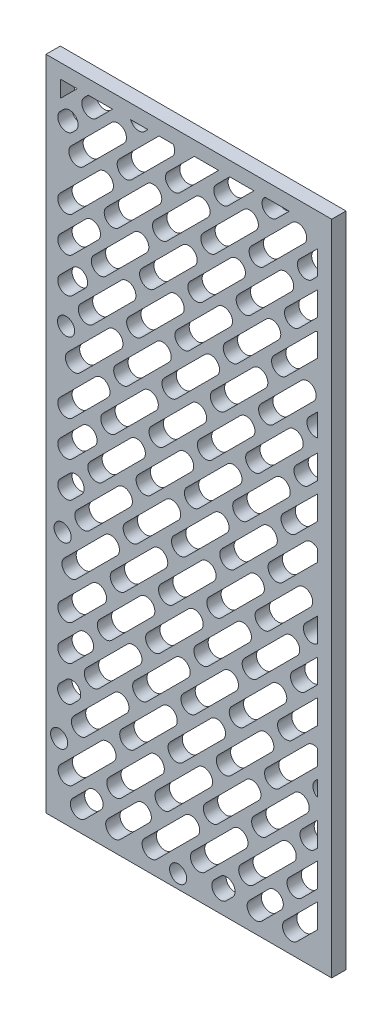
SolidWorks part; units mm, degrees
ref_plane "Front Plane" through (0, 0, 0) normal (0, 0, 1) x (1, 0, 0)
ref_plane "Top Plane" through (0, 0, 0) normal (0, 1, 0) x (1, 0, 0)
ref_plane "Right Plane" through (0, 0, 0) normal (1, 0, 0) x (0, 0, -1)
sketch "Sketch3" plane through (0, 0, 0) normal (0, 0, 1) x (1, 0, 0)
  line L0 (225.2968, 135.1073) -> (405.2968, 135.1073) construction
  line L1 (215.2968, 125.1073) -> (415.2968, 125.1073)
  line L2 (215.2968, 125.1073) -> (215.2968, 585.1073)
  line L3 (215.2968, 585.1073) -> (415.2968, 585.1073)
  line L4 (415.2968, 125.1073) -> (415.2968, 585.1073)
  line L5 (215.2968, 125.1073) -> (415.2968, 585.1073) construction
  line L6 (215.2968, 585.1073) -> (415.2968, 125.1073) construction
  line L7 (405.2968, 135.1073) -> (405.2968, 575.1073) construction
  line L8 (225.2968, 575.1073) -> (405.2968, 575.1073) construction
  line L9 (225.2968, 135.1073) -> (225.2968, 575.1073) construction
  point P0 (315.2968, 355.1073)
  dimension "D1" = 460
  dimension "D2" = 200
sketch "Sketch4" plane through (0, 0, 0) normal (0, 0, 1) x (1, 0, 0)
  line L0 (38.0501, 4.816) -> (66.3343, 33.1003) [skipped]
  line L1 (393.063, 550.0405) -> (405.3813, 562.2146)
  line L2 (405.2968, 545.3575) -> (401.5232, 541.5303)
  line L3 (29.5898, 13.3262) -> (57.849, 41.5856) [skipped]
  line L4 (71.8575, 13.8747) -> (100.1417, 42.159) [skipped]
  line L5 (63.3972, 22.3849) -> (91.6564, 50.6443) [skipped]
  line L6 (105.6649, 22.9333) -> (133.9491, 51.2176) [skipped]
  line L7 (97.2047, 31.4436) -> (125.4638, 59.7029) [skipped]
  line L8 (139.4723, 31.992) -> (167.7565, 60.2763) [skipped]
  line L9 (131.0121, 40.5022) -> (159.2712, 68.7616) [skipped]
  line L10 (173.2797, 41.0507) -> (201.5639, 69.335) [skipped]
  line L11 (164.8195, 49.5609) -> (193.0786, 77.8203) [skipped]
  line L12 (207.0871, 50.1094) -> (235.3713, 78.3936) [skipped]
  line L13 (198.6269, 58.6196) -> (226.886, 86.8789) [skipped]
  line L14 (240.8945, 59.168) -> (269.1787, 87.4523) [skipped]
  line L15 (232.4343, 67.6782) -> (260.6934, 95.9376) [skipped]
  line L16 (274.7019, 68.2267) -> (302.9861, 96.511) [skipped]
  line L17 (266.2417, 76.7369) -> (294.5008, 104.9963) [skipped]
  line L18 (308.5093, 77.2854) -> (336.7935, 105.5696) [skipped]
  line L19 (300.0491, 85.7956) -> (328.3083, 114.0549) [skipped]
  line L20 (342.3167, 86.344) -> (370.6009, 114.6283) [skipped]
  line L21 (333.8565, 94.8542) -> (362.1157, 123.1136) [skipped]
  line L22 (376.1241, 95.4027) -> (404.4084, 123.687) [skipped]
  line L23 (367.6639, 103.9129) -> (395.9231, 132.1723) [skipped]
  line L24 (409.9315, 104.4614) -> (438.2158, 132.7456) [skipped]
  line L25 (401.4713, 112.9716) -> (429.7305, 141.2309) [skipped]
  line L26 (13.3013, 29.5648) -> (41.5856, 57.849) [skipped]
  line L27 (4.8411, 38.075) -> (33.1003, 66.3343) [skipped]
  line L28 (47.1087, 38.6234) -> (75.393, 66.9077) [skipped]
  line L29 (38.6485, 47.1336) -> (66.9077, 75.393) [skipped]
  line L30 (80.9161, 47.6821) -> (109.2004, 75.9664) [skipped]
  line L31 (72.4559, 56.1923) -> (100.7151, 84.4517) [skipped]
  line L32 (114.7235, 56.7408) -> (143.0078, 85.025) [skipped]
  line L33 (106.2633, 65.251) -> (134.5225, 93.5103) [skipped]
  line L34 (148.5309, 65.7994) -> (176.8152, 94.0837) [skipped]
  line L35 (140.0707, 74.3096) -> (168.3299, 102.569) [skipped]
  line L36 (182.3383, 74.8581) -> (210.6226, 103.1424) [skipped]
  line L37 (173.8781, 83.3683) -> (202.1373, 111.6277) [skipped]
  line L38 (216.1457, 83.9168) -> (244.43, 112.201) [skipped]
  line L39 (207.6855, 92.427) -> (235.9447, 120.6863) [skipped]
  line L40 (249.9531, 92.9754) -> (278.2374, 121.2597) [skipped]
  line L41 (241.4929, 101.4856) -> (269.7521, 129.745) [skipped]
  line L42 (234.1022, 143.5926) -> (245.0034, 154.4937)
  line L43 (253.4887, 146.0084) -> (242.5875, 135.1073)
  line L44 (258.8509, 143.5926) -> (278.8108, 163.5524)
  line L45 (287.2961, 155.0671) -> (267.3362, 135.1073)
  line L46 (337.3669, 147.8623) -> (333.0972, 143.5926)
  line L47 (341.5824, 135.1073) -> (345.8522, 139.377)
  line L48 (357.8459, 143.5926) -> (371.1743, 156.921)
  line L49 (379.6596, 148.4357) -> (366.3312, 135.1073)
  line L50 (418.9902, 138.2688) -> (447.2744, 166.553) [skipped]
  line L51 (410.5299, 146.779) -> (438.7891, 175.0383) [skipped]
  line L52 (22.36, 63.3722) -> (50.6442, 91.6564) [skipped]
  line L53 (13.8998, 71.8824) -> (42.1589, 100.1417) [skipped]
  line L54 (56.1674, 72.4308) -> (84.4516, 100.7151) [skipped]
  line L55 (47.7072, 80.941) -> (75.9664, 109.2004) [skipped]
  line L56 (89.9748, 81.4895) -> (118.2591, 109.7738) [skipped]
  line L57 (81.5146, 89.9997) -> (109.7738, 118.2591) [skipped]
  line L58 (123.7822, 90.5482) -> (152.0665, 118.8324) [skipped]
  line L59 (115.322, 99.0584) -> (143.5812, 127.3177) [skipped]
  line L60 (157.5896, 99.6068) -> (185.8739, 127.8911) [skipped]
  line L61 (149.1294, 108.117) -> (177.3886, 136.3764) [skipped]
  line L62 (191.397, 108.6655) -> (219.6813, 136.9498) [skipped]
  line L63 (182.9368, 117.1757) -> (211.196, 145.4351) [skipped]
  line L64 (382.5946, 143.5925) -> (405.2968, 166.2947)
  line L65 (405.2968, 149.3241) -> (391.0799, 135.1073)
  line L66 (405.2968, 135.1073) -> (405.2968, 575.1073) construction
  line L67 (383.4059, 473.9155) -> (405.2968, 495.8065)
  line L68 (292.8192, 135.8415) -> (321.1035, 164.1258)
  line L69 (284.359, 144.3517) -> (312.6182, 172.6111)
  line L70 (326.6266, 144.9002) -> (354.9109, 173.1844)
  line L71 (318.1664, 153.4104) -> (346.4256, 181.6697)
  line L72 (360.434, 153.9588) -> (388.7183, 182.2431)
  line L73 (351.9738, 162.469) -> (380.233, 190.7284)
  line L74 (405.2968, 495.8065) -> (405.2968, 512.0437)
  line L75 (392.4645, 507.7229) -> (405.2968, 520.5552)
  line L76 (428.0488, 172.0762) -> (456.3331, 200.3605) [skipped]
  line L77 (419.5886, 180.5864) -> (447.8478, 208.8457) [skipped]
  line L78 (31.4187, 97.1796) -> (59.7029, 125.4638) [skipped]
  line L79 (22.9584, 105.6898) -> (51.2176, 133.9491) [skipped]
  line L80 (65.2261, 106.2382) -> (93.5103, 134.5225) [skipped]
  line L81 (56.7658, 114.7484) -> (85.025, 143.0078) [skipped]
  line L82 (99.0335, 115.2969) -> (127.3177, 143.5812) [skipped]
  line L83 (90.5732, 123.8071) -> (118.8324, 152.0665) [skipped]
  line L84 (132.8409, 124.3556) -> (161.1251, 152.6398) [skipped]
  line L85 (124.3806, 132.8658) -> (152.6398, 161.1251) [skipped]
  line L86 (166.6483, 133.4142) -> (194.9325, 161.6985) [skipped]
  line L87 (158.1881, 141.9244) -> (186.4472, 170.1838) [skipped]
  line L88 (225.2968, 135.1073) -> (225.2968, 575.1073) construction
  line L89 (236.0217, 549.27) -> (233.7821, 547.0304)
  line L90 (225.2968, 159.5357) -> (254.062, 188.3011)
  line L91 (234.2756, 151.5441) -> (262.5473, 179.8159)
  line L92 (268.0705, 160.5902) -> (296.3547, 188.8745)
  line L93 (259.6103, 169.1004) -> (287.8694, 197.3598)
  line L94 (301.8779, 169.6489) -> (330.1621, 197.9332)
  line L95 (293.4177, 178.1591) -> (321.6768, 206.4185)
  line L96 (335.6853, 178.7076) -> (363.9695, 206.9919)
  line L97 (327.2251, 187.2178) -> (355.4842, 215.4771)
  line L98 (369.4927, 187.7662) -> (397.7769, 216.0505)
  line L99 (361.0325, 196.2764) -> (389.2917, 224.5358)
  line L100 (405.4345, 537.4123) -> (384.0043, 516.2331)
  line L101 (405.4613, 413.6667) -> (381.5771, 390.0622)
  line L102 (437.1075, 205.8836) -> (465.3918, 234.1679) [skipped]
  line L103 (428.6473, 214.3938) -> (456.9065, 242.6531) [skipped]
  line L104 (40.4773, 130.987) -> (68.7616, 159.2712) [skipped]
  line L105 (32.0171, 139.4972) -> (60.2763, 167.7565) [skipped]
  line L106 (74.2847, 140.0456) -> (102.569, 168.3299) [skipped]
  line L107 (65.8245, 148.5558) -> (94.0837, 176.8152) [skipped]
  line L108 (108.0921, 149.1043) -> (136.3764, 177.3886) [skipped]
  line L109 (99.6319, 157.6145) -> (127.8911, 185.8739) [skipped]
  line L110 (141.8995, 158.163) -> (170.1838, 186.4473) [skipped]
  line L111 (133.4393, 166.6732) -> (161.6985, 194.9325) [skipped]
  line L112 (175.7069, 167.2216) -> (203.9912, 195.5059) [skipped]
  line L113 (167.2467, 175.7318) -> (195.5059, 203.9912) [skipped]
  line L114 (227.5364, 557.7553) -> (225.2968, 555.5157)
  line L115 (225.2968, 481.2694) -> (243.2265, 499.1992)
  line L116 (243.3217, 185.339) -> (271.606, 213.6233)
  line L117 (234.8615, 193.8492) -> (263.1207, 222.1085)
  line L118 (277.1291, 194.3976) -> (305.4134, 222.6819)
  line L119 (268.6689, 202.9078) -> (296.9281, 231.1672)
  line L120 (310.9365, 203.4563) -> (339.2208, 231.7406)
  line L121 (302.4763, 211.9665) -> (330.7355, 240.2259)
  line L122 (344.7439, 212.515) -> (373.0282, 240.7993)
  line L123 (336.2837, 221.0252) -> (364.5429, 249.2845)
  line L124 (378.5514, 221.5736) -> (405.2968, 248.3191)
  line L125 (370.0911, 230.0838) -> (398.3503, 258.3432)
  line L126 (412.3588, 230.6323) -> (440.643, 258.9166) [skipped]
  line L127 (403.8985, 239.1425) -> (432.1577, 267.4019) [skipped]
  line L128 (446.1662, 239.691) -> (474.4504, 267.9753) [skipped]
  line L129 (437.7059, 248.2012) -> (465.9651, 276.4606) [skipped]
  line L130 (49.536, 164.7944) -> (77.8202, 193.0787) [skipped]
  line L131 (41.0758, 173.3046) -> (69.3349, 201.5639) [skipped]
  line L132 (83.3434, 173.853) -> (111.6276, 202.1373) [skipped]
  line L133 (74.8832, 182.3632) -> (103.1423, 210.6226) [skipped]
  line L134 (117.1508, 182.9117) -> (145.435, 211.196) [skipped]
  line L135 (108.6906, 191.4219) -> (136.9498, 219.6813) [skipped]
  line L136 (150.9582, 191.9704) -> (179.2425, 220.2547) [skipped]
  line L137 (142.498, 200.4806) -> (170.7572, 228.7399) [skipped]
  line L138 (184.7656, 201.029) -> (213.0499, 229.3133) [skipped]
  line L139 (176.3054, 209.5392) -> (204.5646, 237.7986) [skipped]
  line L140 (251.7118, 490.7139) -> (233.7821, 472.7842)
  line L141 (234.1678, 465.3918) -> (225.2968, 456.5207)
  line L142 (252.3804, 219.1464) -> (280.6647, 247.4307)
  line L143 (243.9202, 227.6566) -> (272.1794, 255.916)
  line L144 (286.1878, 228.205) -> (314.4721, 256.4893)
  line L145 (277.7276, 236.7152) -> (305.9868, 264.9746)
  line L146 (319.9952, 237.2637) -> (348.2795, 265.548)
  line L147 (311.535, 245.7739) -> (339.7942, 274.0333)
  line L148 (353.8026, 246.3224) -> (382.0869, 274.6067)
  line L149 (345.3424, 254.8326) -> (373.6016, 283.092)
  line L150 (390.0373, 381.552) -> (405.2968, 396.8115)
  line L151 (405.2968, 421.5602) -> (399.0959, 415.3594)
  line L152 (421.4174, 264.4397) -> (449.7017, 292.724) [skipped]
  line L153 (412.9572, 272.9499) -> (441.2164, 301.2093) [skipped]
  line L154 (455.2248, 273.4984) -> (483.5091, 301.7827) [skipped]
  line L155 (446.7646, 282.0086) -> (475.0238, 310.268) [skipped]
  line L156 (58.5946, 198.6018) -> (86.8789, 226.8861) [skipped]
  line L157 (50.1344, 207.112) -> (78.3936, 235.3713) [skipped]
  line L158 (92.4021, 207.6604) -> (120.6863, 235.9447) [skipped]
  line L159 (83.9418, 216.1706) -> (112.201, 244.43) [skipped]
  line L160 (126.2095, 216.7191) -> (154.4937, 245.0034) [skipped]
  line L161 (117.7492, 225.2293) -> (146.0084, 253.4887) [skipped]
  line L162 (160.0169, 225.7778) -> (188.3011, 254.0621) [skipped]
  line L163 (151.5566, 234.288) -> (179.8158, 262.5474) [skipped]
  line L164 (193.8243, 234.8364) -> (222.1085, 263.1207) [skipped]
  line L165 (185.364, 243.3466) -> (213.6232, 271.606) [skipped]
  line L166 (233.7821, 448.0354) -> (242.6531, 456.9065)
  line L167 (249.8579, 406.8356) -> (225.2968, 382.2745)
  line L168 (261.4391, 252.9538) -> (289.7233, 281.2381)
  line L169 (252.9789, 261.464) -> (281.238, 289.7234)
  line L170 (295.2465, 262.0124) -> (323.5307, 290.2967)
  line L171 (286.7863, 270.5226) -> (315.0454, 298.782)
  line L172 (329.0539, 271.0711) -> (357.3381, 299.3554)
  line L173 (320.5937, 279.5813) -> (348.8528, 307.8407)
  line L174 (362.8613, 280.1298) -> (391.1455, 308.4141)
  line L175 (354.4011, 288.64) -> (382.6602, 316.8994)
  line L176 (390.6357, 423.8696) -> (405.2968, 438.3589)
  line L177 (387.61, 255.381) -> (405.2968, 273.0678)
  line L178 (430.4761, 298.2471) -> (458.7603, 326.5314) [skipped]
  line L179 (422.0159, 306.7573) -> (450.2751, 335.0167) [skipped]
  line L180 (464.2835, 307.3058) -> (492.5677, 335.5901) [skipped]
  line L181 (455.8233, 315.816) -> (484.0825, 344.0754) [skipped]
  line L182 (67.6533, 232.4092) -> (95.9376, 260.6935) [skipped]
  line L183 (59.1931, 240.9194) -> (87.4523, 269.1788) [skipped]
  line L184 (101.4607, 241.4678) -> (129.745, 269.7521) [skipped]
  line L185 (93.0005, 249.978) -> (121.2597, 278.2374) [skipped]
  line L186 (135.2681, 250.5265) -> (163.5524, 278.8108) [skipped]
  line L187 (126.8079, 259.0367) -> (155.0671, 287.2961) [skipped]
  line L188 (169.0755, 259.5852) -> (197.3598, 287.8695) [skipped]
  line L189 (160.6153, 268.0954) -> (188.8745, 296.3548) [skipped]
  line L190 (233.7821, 373.7892) -> (258.3432, 398.3503)
  line L191 (249.2845, 364.5429) -> (233.7821, 349.0405)
  line L192 (236.6903, 277.7025) -> (264.9746, 305.9868)
  line L193 (228.2301, 286.2127) -> (256.4893, 314.4721)
  line L194 (270.4977, 286.7612) -> (298.782, 315.0455)
  line L195 (262.0375, 295.2714) -> (290.2967, 323.5308)
  line L196 (304.3051, 295.8198) -> (332.5894, 324.1041)
  line L197 (295.8449, 304.3301) -> (324.1041, 332.5894)
  line L198 (338.1125, 304.8785) -> (366.3968, 333.1628)
  line L199 (329.6523, 313.3887) -> (357.9115, 341.6481)
  line L200 (371.9199, 313.9372) -> (400.2042, 342.2215)
  line L201 (363.4597, 322.4474) -> (391.7189, 350.7068)
  line L202 (405.2968, 290.0382) -> (379.1498, 263.8912)
  line L203 (388.2085, 297.6986) -> (405.2968, 314.5868)
  line L204 (439.5348, 332.0545) -> (467.819, 360.3388) [skipped]
  line L205 (431.0745, 340.5647) -> (459.3337, 368.8241) [skipped]
  line L206 (473.3422, 341.1132) -> (501.6264, 369.3975) [skipped]
  line L207 (464.8819, 349.6234) -> (493.1411, 377.8828) [skipped]
  line L208 (76.712, 266.2166) -> (104.9962, 294.5009) [skipped]
  line L209 (68.2518, 274.7268) -> (96.5109, 302.9862) [skipped]
  line L210 (110.5194, 275.2752) -> (138.8036, 303.5595) [skipped]
  line L211 (102.0592, 283.7854) -> (130.3183, 312.0448) [skipped]
  line L212 (144.3268, 284.3339) -> (172.611, 312.6182) [skipped]
  line L213 (135.8666, 292.8441) -> (164.1257, 321.1035) [skipped]
  line L214 (178.1342, 293.3926) -> (206.4184, 321.6769) [skipped]
  line L215 (169.674, 301.9028) -> (197.9332, 330.1622) [skipped]
  line L216 (240.7992, 373.0282) -> (225.2968, 357.5258)
  line L217 (225.2968, 332.7771) -> (231.7406, 339.2208)
  line L218 (245.749, 311.5099) -> (274.0333, 339.7942)
  line L219 (237.2888, 320.0201) -> (265.548, 348.2795)
  line L220 (279.5564, 320.5686) -> (307.8407, 348.8529)
  line L221 (271.0962, 329.0788) -> (299.3554, 357.3382)
  line L222 (313.3638, 329.6273) -> (341.6481, 357.9115)
  line L223 (304.9036, 338.1375) -> (333.1628, 366.3968)
  line L224 (347.1712, 338.6859) -> (375.4555, 366.9702)
  line L225 (338.711, 347.1961) -> (366.9702, 375.4555)
  line L226 (380.9786, 347.7446) -> (405.2968, 372.0628)
  line L227 (372.5184, 356.2548) -> (396.8115, 380.5481)
  line L228 (414.786, 356.8033) -> (443.0703, 385.0875) [skipped]
  line L229 (406.3258, 365.3135) -> (434.585, 393.5728) [skipped]
  line L230 (448.5934, 365.8619) -> (476.8777, 394.1462) [skipped]
  line L231 (440.1332, 374.3721) -> (468.3924, 402.6315) [skipped]
  line L232 (482.4008, 374.9206) -> (510.6851, 403.2049) [skipped]
  line L233 (473.9406, 383.4308) -> (502.1998, 411.6902) [skipped]
  line L234 (85.7706, 300.024) -> (114.0549, 328.3083) [skipped]
  line L235 (77.3104, 308.5342) -> (105.5696, 336.7936) [skipped]
  line L236 (119.578, 309.0827) -> (147.8623, 337.3669) [skipped]
  line L237 (111.1178, 317.5929) -> (139.377, 345.8522) [skipped]
  line L238 (153.3855, 318.1413) -> (181.6697, 346.4256) [skipped]
  line L239 (144.9252, 326.6515) -> (173.1844, 354.9109) [skipped]
  line L240 (187.1929, 327.2) -> (215.4771, 355.4843) [skipped]
  line L241 (178.7326, 335.7102) -> (206.9918, 363.9696) [skipped]
  line L242 (233.7821, 324.2917) -> (240.2259, 330.7355)
  line L243 (225.2968, 258.5308) -> (247.4306, 280.6647)
  line L244 (254.8077, 345.3173) -> (283.0919, 373.6016)
  line L245 (246.3474, 353.8275) -> (274.6066, 382.0869)
  line L246 (288.6151, 354.376) -> (316.8993, 382.6603)
  line L247 (280.1549, 362.8862) -> (308.414, 391.1456)
  line L248 (322.4225, 363.4347) -> (350.7067, 391.7189)
  line L249 (313.9623, 371.9449) -> (342.2214, 400.2042)
  line L250 (356.2299, 372.4933) -> (384.5141, 400.7776)
  line L251 (347.7697, 381.0035) -> (376.0288, 409.2629)
  line L252 (405.2968, 297.8165) -> (396.6687, 289.1884)
  line L253 (394.2414, 163.0175) -> (405.2968, 174.0729)
  line L254 (423.8447, 390.6107) -> (452.1289, 418.8949) [skipped]
  line L255 (415.3845, 399.1209) -> (443.6436, 427.3802) [skipped]
  line L256 (457.6521, 399.6693) -> (485.9363, 427.9536) [skipped]
  line L257 (449.1919, 408.1795) -> (477.451, 436.4389) [skipped]
  line L258 (491.4595, 408.728) -> (519.7437, 437.0123) [skipped]
  line L259 (482.9993, 417.2382) -> (511.2585, 445.4976) [skipped]
  line L260 (94.8293, 333.8314) -> (123.1136, 362.1157) [skipped]
  line L261 (86.3691, 342.3416) -> (114.6283, 370.601) [skipped]
  line L262 (128.6367, 342.8901) -> (156.921, 371.1743) [skipped]
  line L263 (120.1765, 351.4003) -> (148.4357, 379.6596) [skipped]
  line L264 (162.4441, 351.9487) -> (190.7284, 380.233) [skipped]
  line L265 (153.9839, 360.4589) -> (182.2431, 388.7183) [skipped]
  line L266 (196.2515, 361.0074) -> (224.5358, 389.2917) [skipped]
  line L267 (187.7913, 369.5176) -> (216.0505, 397.777) [skipped]
  line L268 (233.7821, 250.0455) -> (255.9159, 272.1794)
  line L269 (233.7821, 225.2968) -> (246.8573, 238.372)
  line L270 (263.8663, 379.1247) -> (292.1506, 407.409)
  line L271 (255.4061, 387.6349) -> (283.6653, 415.8943)
  line L272 (297.6737, 388.1834) -> (325.958, 416.4677)
  line L273 (289.2135, 396.6936) -> (317.4727, 424.953)
  line L274 (331.4811, 397.2421) -> (359.7654, 425.5263)
  line L275 (323.0209, 405.7523) -> (351.2801, 434.0116)
  line L276 (365.2885, 406.3007) -> (393.5728, 434.585)
  line L277 (356.8283, 414.8109) -> (385.0875, 443.0703)
  line L278 (405.2968, 191.0433) -> (385.7812, 171.5277)
  line L279 (403.3001, 196.8249) -> (405.2968, 198.8216)
  line L280 (432.9033, 424.4181) -> (461.1876, 452.7024) [skipped]
  line L281 (424.4431, 432.9283) -> (452.7023, 461.1876) [skipped]
  line L282 (466.7107, 433.4767) -> (494.995, 461.761) [skipped]
  line L283 (458.2505, 441.9869) -> (486.5097, 470.2463) [skipped]
  line L284 (500.5182, 442.5354) -> (528.8024, 470.8197) [skipped]
  line L285 (492.0579, 451.0456) -> (520.3171, 479.305) [skipped]
  line L286 (103.888, 367.6388) -> (132.1722, 395.9231) [skipped]
  line L287 (95.4278, 376.149) -> (123.6869, 404.4084) [skipped]
  line L288 (137.6954, 376.6975) -> (165.9796, 404.9817) [skipped]
  line L289 (129.2352, 385.2077) -> (157.4943, 413.467) [skipped]
  line L290 (171.5028, 385.7561) -> (199.787, 414.0404) [skipped]
  line L291 (163.0426, 394.2663) -> (191.3017, 422.5257) [skipped]
  line L292 (238.372, 246.8573) -> (225.2968, 233.7821)
  line L293 (225.2968, 209.0333) -> (229.3133, 213.0499)
  line L294 (239.1176, 403.8735) -> (267.4018, 432.1577)
  line L295 (230.6574, 412.3837) -> (258.9166, 440.643)
  line L296 (272.925, 412.9321) -> (301.2093, 441.2164)
  line L297 (264.4648, 421.4423) -> (292.724, 449.7017)
  line L298 (306.7324, 421.9908) -> (335.0167, 450.2751)
  line L299 (298.2722, 430.501) -> (326.5314, 458.7604)
  line L300 (340.5398, 431.0495) -> (368.8241, 459.3338)
  line L301 (332.0796, 439.5597) -> (360.3388, 467.819)
  line L302 (374.3472, 440.1081) -> (402.6315, 468.3924)
  line L303 (365.887, 448.6183) -> (394.1462, 476.8777)
  line L304 (405.2968, 215.792) -> (394.8399, 205.3351)
  line L305 (233.5559, 200.3219) -> (237.7986, 204.5646)
  line L306 (441.962, 458.2255) -> (470.2463, 486.5098) [skipped]
  line L307 (433.5018, 466.7357) -> (461.761, 494.995) [skipped]
  line L308 (475.7694, 467.2841) -> (504.0537, 495.5684) [skipped]
  line L309 (467.3092, 475.7943) -> (495.5684, 504.0537) [skipped]
  line L310 (509.5768, 476.3428) -> (537.8611, 504.6271) [skipped]
  line L311 (501.1166, 484.853) -> (529.3758, 513.1124) [skipped]
  line L312 (112.9466, 401.4462) -> (141.2309, 429.7305) [skipped]
  line L313 (104.4864, 409.9564) -> (132.7456, 438.2158) [skipped]
  line L314 (146.754, 410.5049) -> (175.0383, 438.7892) [skipped]
  line L315 (138.2938, 419.0151) -> (166.553, 447.2744) [skipped]
  line L316 (180.5614, 419.5635) -> (208.8457, 447.8478) [skipped]
  line L317 (172.1012, 428.0737) -> (200.3604, 456.3331) [skipped]
  line L319 (225.2968, 563.2938) -> (225.2968, 575.1073)
  line L320 (248.1763, 437.6809) -> (276.4605, 465.9652)
  line L321 (239.716, 446.1911) -> (267.9752, 474.4504)
  line L322 (281.9837, 446.7395) -> (310.2679, 475.0238)
  line L323 (273.5234, 455.2497) -> (301.7826, 483.5091)
  line L324 (315.7911, 455.7982) -> (344.0753, 484.0825)
  line L325 (307.3308, 464.3084) -> (335.59, 492.5678)
  line L326 (349.5985, 464.8569) -> (377.8827, 493.1412)
  line L327 (341.1383, 473.3671) -> (369.3974, 501.6264)
  line L328 (225.2968, 575.1073) -> (237.1102, 575.1073)
  line L329 (261.859, 575.1073) -> (244.8885, 575.1073)
  line L330 (417.2133, 482.9742) -> (445.4975, 511.2585) [skipped]
  line L331 (408.7531, 491.4844) -> (437.0122, 519.7438) [skipped]
  line L332 (451.0207, 492.0329) -> (479.3049, 520.3172) [skipped]
  line L333 (442.5605, 500.5431) -> (470.8196, 528.8025) [skipped]
  line L334 (484.8281, 501.0915) -> (513.1123, 529.3758) [skipped]
  line L335 (476.3679, 509.6017) -> (504.627, 537.8611) [skipped]
  line L336 (518.6355, 510.1502) -> (546.9197, 538.4345) [skipped]
  line L337 (510.1753, 518.6604) -> (538.4344, 546.9198) [skipped]
  line L338 (122.0053, 435.2536) -> (150.2896, 463.5379) [skipped]
  line L339 (113.5451, 443.7638) -> (141.8043, 472.0232) [skipped]
  line L340 (155.8127, 444.3123) -> (184.097, 472.5966) [skipped]
  line L341 (147.3525, 452.8225) -> (175.6117, 481.0818) [skipped]
  line L342 (189.6201, 453.3709) -> (217.9044, 481.6552) [skipped]
  line L343 (181.1599, 461.8811) -> (209.4191, 490.1405) [skipped]
  line L344 (225.2968, 575.1073) -> (405.2968, 575.1073) construction
  line L345 (274.5278, 575.1073) -> (286.6077, 575.1073)
  line L346 (257.2349, 471.4883) -> (285.5192, 499.7726)
  line L347 (248.7747, 479.9985) -> (277.0339, 508.2578)
  line L348 (291.0423, 480.5469) -> (319.3266, 508.8312)
  line L349 (282.5821, 489.0571) -> (310.8413, 517.3165)
  line L350 (324.8497, 489.6056) -> (353.134, 517.8899)
  line L351 (316.3895, 498.1158) -> (344.6487, 526.3752)
  line L352 (358.6571, 498.6643) -> (386.9414, 526.9486)
  line L353 (350.1969, 507.1745) -> (378.4561, 535.4339)
  line L354 (294.3858, 575.1073) -> (304.2835, 575.1073)
  line L355 (319.1346, 575.1073) -> (336.1052, 575.1073)
  line L356 (426.2719, 516.7816) -> (454.5562, 545.0659) [skipped]
  line L357 (417.8117, 525.2918) -> (446.0709, 553.5512) [skipped]
  line L358 (460.0793, 525.8403) -> (488.3636, 554.1246) [skipped]
  line L359 (451.6191, 534.3505) -> (479.8783, 562.6099) [skipped]
  line L360 (493.8867, 534.8989) -> (522.171, 563.1832) [skipped]
  line L361 (485.4265, 543.4091) -> (513.6857, 571.6685) [skipped]
  line L362 (527.6941, 543.9576) -> (555.9784, 572.2419) [skipped]
  line L363 (519.2339, 552.4678) -> (547.4931, 580.7272) [skipped]
  line L364 (131.064, 469.061) -> (159.3482, 497.3453) [skipped]
  line L365 (122.6038, 477.5712) -> (150.8629, 505.8306) [skipped]
  line L366 (164.8714, 478.1197) -> (193.1556, 506.404) [skipped]
  line L367 (156.4112, 486.6299) -> (184.6703, 514.8893) [skipped]
  line L368 (198.6788, 487.1783) -> (226.963, 515.4626) [skipped]
  line L369 (190.2186, 495.6885) -> (218.4777, 523.9479) [skipped]
  line L370 (233.7821, 497.5329) -> (260.7704, 524.5213)
  line L371 (225.2968, 506.018) -> (252.2851, 533.0066)
  line L372 (266.2936, 505.2957) -> (294.5778, 533.58)
  line L373 (257.8334, 513.8059) -> (286.0925, 542.0653)
  line L374 (300.101, 514.3543) -> (328.3852, 542.6386)
  line L375 (291.6408, 522.8645) -> (319.9, 551.1239)
  line L376 (333.9084, 523.413) -> (362.1927, 551.6973)
  line L377 (325.4482, 531.9232) -> (353.7074, 560.1826)
  line L378 (367.7158, 532.4717) -> (396.0001, 560.756)
  line L379 (359.2556, 540.9819) -> (387.5148, 569.2413)
  line L380 (343.8834, 575.1073) -> (360.8539, 575.1073)
  line L381 (385.6026, 575.1073) -> (368.6322, 575.1072)
  line L382 (435.3306, 550.589) -> (463.6149, 578.8733) [skipped]
  line L383 (426.8704, 559.0992) -> (455.1296, 587.3586) [skipped]
  line L384 (469.138, 559.6477) -> (497.4223, 587.932) [skipped]
  line L385 (460.6778, 568.1579) -> (488.937, 596.4173) [skipped]
  line L386 (502.9454, 568.7063) -> (531.2297, 596.9906) [skipped]
  line L387 (494.4852, 577.2166) -> (522.7444, 605.4759) [skipped]
  line L388 (536.7528, 577.765) -> (565.0371, 606.0493) [skipped]
  line L389 (528.2926, 586.2752) -> (556.5518, 614.5346) [skipped]
  line L390 (140.1226, 502.8684) -> (168.4069, 531.1527) [skipped]
  line L391 (131.6624, 511.3786) -> (159.9216, 539.638) [skipped]
  line L392 (173.93, 511.9271) -> (202.2143, 540.2114) [skipped]
  line L393 (165.4698, 520.4373) -> (193.729, 548.6967) [skipped]
  line L394 (405.2968, 545.3575) -> (405.3813, 562.2146)
  line L395 (405.2968, 520.5552) -> (405.4345, 537.4123)
  line L396 (241.5448, 530.0444) -> (269.8291, 558.3287)
  line L397 (233.0846, 538.5546) -> (261.3438, 566.814)
  line L398 (275.3523, 539.1031) -> (303.6365, 567.3874)
  line L399 (266.892, 547.6133) -> (294.3858, 575.1073)
  line L400 (309.1597, 548.1617) -> (336.1052, 575.1073)
  line L401 (300.6994, 556.6719) -> (319.1346, 575.1073)
  line L402 (342.9671, 557.2204) -> (360.8539, 575.1073)
  line L403 (334.5068, 565.7306) -> (343.8834, 575.1073)
  line L404 (376.7745, 566.2791) -> (385.6026, 575.1073)
  line L405 (368.3142, 574.7893) -> (368.6322, 575.1072)
  line L406 (410.5819, 575.3378) -> (438.8661, 603.622) [skipped]
  line L407 (402.1217, 583.848) -> (430.3808, 612.1073) [skipped]
  line L408 (444.3893, 584.3964) -> (472.6735, 612.6807) [skipped]
  line L409 (435.9291, 592.9066) -> (464.1882, 621.166) [skipped]
  line L410 (478.1967, 593.4551) -> (506.4809, 621.7394) [skipped]
  line L411 (469.7365, 601.9653) -> (497.9956, 630.2246) [skipped]
  line L412 (512.0041, 602.5138) -> (540.2883, 630.798) [skipped]
  line L413 (503.5439, 611.024) -> (531.803, 639.2833) [skipped]
  line L414 (545.8115, 611.5724) -> (574.0957, 639.8567) [skipped]
  line L415 (537.3513, 620.0826) -> (565.6104, 648.342) [skipped]
  line L416 (149.1813, 536.6758) -> (177.4656, 564.9601) [skipped]
  line L417 (140.7211, 545.186) -> (168.9803, 573.4454) [skipped]
  line L418 (182.9887, 545.7345) -> (211.273, 574.0188) [skipped]
  line L419 (174.5285, 554.2447) -> (202.7877, 582.5041) [skipped]
  line L420 (225.2968, 563.2938) -> (237.1102, 575.1073)
  line L421 (405.2968, 447.5714) -> (405.2968, 463.2795)
  line L422 (250.6035, 563.8518) -> (261.859, 575.1073)
  line L423 (242.1433, 572.362) -> (244.8885, 575.1073)
  line L424 (284.4109, 572.9105) -> (286.6077, 575.1073)
  line L425 (405.2968, 421.5602) -> (405.2968, 438.3589)
  line L426 (318.2183, 581.9692) -> (346.5026, 610.2534) [skipped]
  line L427 (309.7581, 590.4794) -> (338.0173, 618.7387) [skipped]
  line L428 (352.0257, 591.0278) -> (380.31, 619.3121) [skipped]
  line L429 (343.5655, 599.538) -> (371.8247, 627.7974) [skipped]
  line L430 (385.8331, 600.0865) -> (414.1174, 628.3708) [skipped]
  line L431 (377.3729, 608.5967) -> (405.6321, 636.8561) [skipped]
  line L432 (419.6405, 609.1452) -> (447.9248, 637.4294) [skipped]
  line L433 (411.1803, 617.6554) -> (439.4395, 645.9147) [skipped]
  line L434 (453.4479, 618.2038) -> (481.7322, 646.4881) [skipped]
  line L435 (444.9877, 626.714) -> (473.2469, 654.9734) [skipped]
  line L436 (487.2553, 627.2625) -> (515.5396, 655.5468) [skipped]
  line L437 (478.7951, 635.7727) -> (507.0543, 664.0321) [skipped]
  line L438 (521.0627, 636.3212) -> (549.347, 664.6054) [skipped]
  line L439 (512.6025, 644.8314) -> (540.8617, 673.0907) [skipped]
  line L440 (554.8701, 645.3798) -> (583.1544, 673.6641) [skipped]
  line L441 (546.4099, 653.89) -> (574.6691, 682.1494) [skipped]
  line L442 (158.24, 570.4832) -> (186.5242, 598.7675) [skipped]
  line L443 (149.7798, 578.9934) -> (178.0389, 607.2528) [skipped]
  line L444 (192.0474, 579.5419) -> (220.3316, 607.8262) [skipped]
  line L445 (183.5872, 588.0521) -> (211.8463, 616.3115) [skipped]
  line L446 (225.8548, 588.6006) -> (254.139, 616.8848) [skipped]
  line L447 (217.3946, 597.1108) -> (245.6537, 625.3701) [skipped]
  line L448 (259.6622, 597.6592) -> (287.9464, 625.9435) [skipped]
  line L449 (251.202, 606.1694) -> (279.4611, 634.4288) [skipped]
  line L450 (293.4696, 606.7179) -> (321.7538, 635.0022) [skipped]
  line L451 (285.0094, 615.2281) -> (313.2685, 643.4875) [skipped]
  line L452 (327.277, 615.7766) -> (355.5612, 644.0608) [skipped]
  line L453 (318.8168, 624.2868) -> (347.0759, 652.5461) [skipped]
  line L454 (361.0844, 624.8352) -> (389.3686, 653.1195) [skipped]
  line L455 (352.6242, 633.3454) -> (380.8834, 661.6048) [skipped]
  line L456 (394.8918, 633.8939) -> (423.1761, 662.1782) [skipped]
  line L457 (386.4316, 642.4041) -> (414.6908, 670.6635) [skipped]
  line L458 (428.6992, 642.9526) -> (456.9835, 671.2368) [skipped]
  line L459 (420.239, 651.4628) -> (448.4982, 679.7221) [skipped]
  line L460 (462.5066, 652.0112) -> (490.7909, 680.2955) [skipped]
  line L461 (454.0464, 660.5214) -> (482.3056, 688.7808) [skipped]
  line L462 (496.314, 661.0699) -> (524.5983, 689.3542) [skipped]
  line L463 (487.8538, 669.5801) -> (516.113, 697.8395) [skipped]
  line L464 (530.1214, 670.1286) -> (558.4057, 698.4128) [skipped]
  line L465 (521.6612, 678.6388) -> (549.9204, 706.8981) [skipped]
  line L466 (563.9288, 679.1872) -> (592.2131, 707.4715) [skipped]
  line L467 (555.4686, 687.6974) -> (583.7278, 715.9568) [skipped]
  line L468 (225.2968, 135.1073) -> (405.2968, 135.1073) construction
  line L470 (399.6693, 457.6521) -> (405.2968, 463.2795)
  line L471 (405.2968, 396.8115) -> (405.4613, 413.6667)
  line L472 (374.9457, 482.4257) -> (403.2299, 510.71)
  line L473 (283.7605, 102.0341) -> (312.0448, 130.3184) [skipped]
  line L474 (275.3003, 110.5443) -> (303.5595, 138.8037) [skipped]
  line L475 (317.568, 111.0928) -> (345.8522, 139.377) [skipped]
  line L476 (309.1077, 119.603) -> (337.3669, 147.8623) [skipped]
  line L477 (351.3754, 120.1514) -> (379.6596, 148.4357) [skipped]
  line L478 (342.9151, 128.6616) -> (371.1743, 156.921) [skipped]
  line L479 (385.1828, 129.2101) -> (413.467, 157.4944) [skipped]
  line L480 (376.7225, 137.7203) -> (404.9817, 165.9797) [skipped]
  line L481 (225.2044, 117.7242) -> (253.4887, 146.0084) [skipped]
  line L482 (216.7442, 126.2344) -> (245.0034, 154.4937) [skipped]
  line L483 (259.0118, 126.7828) -> (287.2961, 155.0671) [skipped]
  line L484 (250.5516, 135.293) -> (278.8108, 163.5524) [skipped]
  line L485 (4.2427, -4.2427) -> (32.5269, 24.0416) [skipped]
  line L486 (-4.2176, 4.2675) -> (24.0416, 32.5269) [skipped]
  line L487 (394.2414, 163.0175) -> (422.5257, 191.3018) [skipped]
  line L488 (385.7812, 171.5277) -> (414.0404, 199.7871) [skipped]
  line L489 (403.3001, 196.8249) -> (431.5843, 225.1092) [skipped]
  line L490 (394.8399, 205.3351) -> (423.0991, 233.5945) [skipped]
  line L491 (387.61, 255.381) -> (415.8943, 283.6653) [skipped]
  line L492 (379.1498, 263.8912) -> (407.409, 292.1506) [skipped]
  line L493 (396.6687, 289.1884) -> (424.9529, 317.4727) [skipped]
  line L494 (388.2085, 297.6986) -> (416.4676, 325.958) [skipped]
  line L495 (405.7273, 322.9959) -> (434.0116, 351.2801) [skipped]
  line L496 (397.2671, 331.5061) -> (425.5263, 359.7654) [skipped]
  line L497 (390.0373, 381.552) -> (418.3215, 409.8363) [skipped]
  line L498 (381.5771, 390.0622) -> (409.8362, 418.3216) [skipped]
  line L499 (399.0959, 415.3594) -> (427.3802, 443.6437) [skipped]
  line L500 (390.6357, 423.8696) -> (418.8949, 452.129) [skipped]
  line L501 (408.1546, 449.1668) -> (436.4389, 477.4511) [skipped]
  line L502 (399.6944, 457.677) -> (427.9536, 485.9364) [skipped]
  line L503 (374.9457, 482.4257) -> (403.2048, 510.6851) [skipped]
  line L504 (383.4059, 473.9155) -> (411.6901, 502.1998) [skipped]
  line L505 (392.4645, 507.7229) -> (420.7488, 536.0072) [skipped]
  line L506 (384.0043, 516.2331) -> (412.2635, 544.4925) [skipped]
  line L507 (401.5232, 541.5303) -> (429.8075, 569.8146) [skipped]
  line L508 (393.063, 550.0405) -> (421.3222, 578.2999) [skipped]
  line L509 (200.4557, 142.4729) -> (228.7399, 170.7572) [skipped]
  line L510 (191.9955, 150.9831) -> (220.2546, 179.2425) [skipped]
  line L511 (209.5143, 176.2803) -> (237.7986, 204.5646) [skipped]
  line L512 (201.0541, 184.7905) -> (229.3133, 213.0499) [skipped]
  line L513 (218.573, 210.0877) -> (246.8573, 238.372) [skipped]
  line L514 (210.1128, 218.5979) -> (238.372, 246.8573) [skipped]
  line L515 (227.6317, 243.8951) -> (255.9159, 272.1794) [skipped]
  line L516 (219.1715, 252.4053) -> (247.4306, 280.6647) [skipped]
  line L517 (202.8829, 268.6438) -> (231.1672, 296.9281) [skipped]
  line L518 (194.4227, 277.154) -> (222.6819, 305.4134) [skipped]
  line L519 (211.9416, 302.4513) -> (240.2259, 330.7355) [skipped]
  line L520 (203.4814, 310.9615) -> (231.7406, 339.2208) [skipped]
  line L521 (221.0003, 336.2587) -> (249.2845, 364.5429) [skipped]
  line L522 (212.54, 344.7689) -> (240.7992, 373.0282) [skipped]
  line L523 (230.0589, 370.0661) -> (258.3432, 398.3503) [skipped]
  line L524 (221.5987, 378.5763) -> (249.8579, 406.8356) [skipped]
  line L525 (205.3102, 394.8148) -> (233.5944, 423.0991) [skipped]
  line L526 (196.85, 403.325) -> (225.1091, 431.5844) [skipped]
  line L527 (214.3689, 428.6222) -> (242.6531, 456.9065) [skipped]
  line L528 (205.9086, 437.1324) -> (234.1678, 465.3918) [skipped]
  line L529 (223.4275, 462.4296) -> (251.7118, 490.7139) [skipped]
  line L530 (214.9673, 470.9398) -> (243.2265, 499.1992) [skipped]
  line L531 (207.7374, 520.9857) -> (236.0217, 549.27) [skipped]
  line L532 (199.2772, 529.4959) -> (227.5364, 557.7553) [skipped]
  line L533 (208.3359, 563.3033) -> (236.5951, 591.5627) [skipped]
  line L534 (275.9507, 581.4207) -> (304.2099, 609.6801) [skipped]
  line L535 (405.2968, 372.0628) -> (405.2968, 380.5481)
  line L536 (405.2968, 297.8165) -> (405.2968, 314.5868)
  line L537 (397.2671, 331.5061) -> (405.2968, 339.5358)
  line L538 (405.2968, 339.5358) -> (405.2968, 322.6051)
  line L539 (405.2968, 273.0678) -> (405.2968, 290.0382)
  line L540 (405.2968, 248.3191) -> (405.2968, 259.4568)
  line L541 (405.2968, 198.8216) -> (405.2968, 215.792)
  line L542 (378.5514, 221.5736) -> (405.2968, 248.3191) [skipped]
  line L543 (370.0911, 230.0838) -> (396.8115, 256.8044) [skipped]
  line L544 (405.2968, 174.0729) -> (405.2968, 191.0433)
  line L545 (403.8985, 239.1425) -> (405.2968, 240.5244)
  line L547 (405.2968, 240.5244) -> (405.2968, 229.5786)
  line L550 (234.2631, 151.5316) -> (262.5473, 179.8159) [skipped]
  line L551 (225.8029, 160.0418) -> (254.062, 188.3011) [skipped]
  line L552 (405.2968, 149.3241) -> (405.2968, 166.2947)
  arc A0 (29.5898, 13.3262) -> (38.0501, 4.816) centre (33.8074, 9.0587) ccw [skipped]
  arc A1 (57.849, 41.5856) -> (66.3343, 33.1003) centre (62.0917, 37.3429) cw [skipped]
  arc A2 (403.8985, 239.1425) -> (405.2968, 229.5786) centre (408.1161, 234.8749) ccw
  arc A3 (225.2968, 209.0333) -> (233.5559, 200.3219) centre (229.4264, 204.6776) ccw
  arc A4 (63.3972, 22.3849) -> (71.8575, 13.8747) centre (67.6148, 18.1173) ccw [skipped]
  arc A5 (91.6564, 50.6443) -> (100.1417, 42.159) centre (95.8991, 46.4016) cw [skipped]
  arc A6 (97.2047, 31.4436) -> (105.6649, 22.9333) centre (101.4222, 27.176) ccw [skipped]
  arc A7 (125.4638, 59.7029) -> (133.9491, 51.2176) centre (129.7065, 55.4603) cw [skipped]
  arc A8 (131.0121, 40.5022) -> (139.4723, 31.992) centre (135.2296, 36.2347) ccw [skipped]
  arc A9 (159.2712, 68.7616) -> (167.7565, 60.2763) centre (163.5139, 64.5189) cw [skipped]
  arc A10 (164.8195, 49.5609) -> (173.2797, 41.0507) centre (169.037, 45.2933) ccw [skipped]
  arc A11 (193.0786, 77.8203) -> (201.5639, 69.335) centre (197.3213, 73.5776) cw [skipped]
  arc A12 (198.6269, 58.6196) -> (207.0871, 50.1094) centre (202.8444, 54.352) ccw [skipped]
  arc A13 (226.886, 86.8789) -> (235.3713, 78.3936) centre (231.1287, 82.6363) cw [skipped]
  arc A14 (232.4343, 67.6782) -> (240.8945, 59.168) centre (236.6518, 63.4107) ccw [skipped]
  arc A15 (260.6934, 95.9376) -> (269.1787, 87.4523) centre (264.9361, 91.695) cw [skipped]
  arc A16 (266.2417, 76.7369) -> (274.7019, 68.2267) centre (270.4592, 72.4693) ccw [skipped]
  arc A17 (294.5008, 104.9963) -> (302.9861, 96.511) centre (298.7435, 100.7536) cw [skipped]
  arc A18 (300.0491, 85.7956) -> (308.5093, 77.2854) centre (304.2666, 81.528) ccw [skipped]
  arc A19 (328.3083, 114.0549) -> (336.7935, 105.5696) centre (332.5509, 109.8123) cw [skipped]
  arc A20 (333.8565, 94.8542) -> (342.3167, 86.344) centre (338.074, 90.5867) ccw [skipped]
  arc A21 (362.1157, 123.1136) -> (370.6009, 114.6283) centre (366.3583, 118.871) cw [skipped]
  arc A22 (367.6639, 103.9129) -> (376.1241, 95.4027) centre (371.8815, 99.6453) ccw [skipped]
  arc A23 (395.9231, 132.1723) -> (404.4084, 123.687) centre (400.1657, 127.9296) cw [skipped]
  arc A24 (401.4713, 112.9716) -> (409.9315, 104.4614) centre (405.6889, 108.704) ccw [skipped]
  arc A25 (429.7305, 141.2309) -> (438.2158, 132.7456) centre (433.9731, 136.9883) cw [skipped]
  arc A26 (4.8411, 38.075) -> (13.3013, 29.5648) centre (9.0587, 33.8074) ccw [skipped]
  arc A27 (33.1003, 66.3343) -> (41.5856, 57.849) centre (37.3429, 62.0917) cw [skipped]
  arc A28 (38.6485, 47.1336) -> (47.1087, 38.6234) centre (42.8661, 42.8661) ccw [skipped]
  arc A29 (66.9077, 75.393) -> (75.393, 66.9077) centre (71.1503, 71.1503) cw [skipped]
  arc A30 (72.4559, 56.1923) -> (80.9161, 47.6821) centre (76.6735, 51.9247) ccw [skipped]
  arc A31 (100.7151, 84.4517) -> (109.2004, 75.9664) centre (104.9577, 80.209) cw [skipped]
  arc A32 (106.2633, 65.251) -> (114.7235, 56.7408) centre (110.4809, 60.9834) ccw [skipped]
  arc A33 (134.5225, 93.5103) -> (143.0078, 85.025) centre (138.7651, 89.2677) cw [skipped]
  arc A34 (140.0707, 74.3096) -> (148.5309, 65.7994) centre (144.2883, 70.0421) ccw [skipped]
  arc A35 (168.3299, 102.569) -> (176.8152, 94.0837) centre (172.5725, 98.3264) cw [skipped]
  arc A36 (173.8781, 83.3683) -> (182.3383, 74.8581) centre (178.0957, 79.1007) ccw [skipped]
  arc A37 (202.1373, 111.6277) -> (210.6226, 103.1424) centre (206.3799, 107.385) cw [skipped]
  arc A38 (207.6855, 92.427) -> (216.1457, 83.9168) centre (211.9031, 88.1594) ccw [skipped]
  arc A39 (235.9447, 120.6863) -> (244.43, 112.201) centre (240.1874, 116.4437) cw [skipped]
  arc A40 (241.4929, 101.4856) -> (249.9531, 92.9754) centre (245.7105, 97.2181) ccw [skipped]
  arc A41 (269.7521, 129.745) -> (278.2374, 121.2597) centre (273.9948, 125.5024) cw [skipped]
  circle A42 centre (307.8022, 134.561) radius 6
  arc A43 (398.3503, 258.3432) -> (405.2968, 259.4568) centre (402.593, 254.1006) cw
  arc A44 (391.0799, 135.1073) -> (382.5946, 143.5925) centre (386.8373, 139.3499) cw
  arc A45 (337.3669, 147.8623) -> (345.8522, 139.377) centre (341.6096, 143.6197) cw
  arc A46 (225.2968, 159.5357) -> (234.2756, 151.5441) centre (229.7862, 155.5399) ccw
  arc A47 (371.1743, 156.921) -> (379.6596, 148.4357) centre (375.417, 152.6784) cw
  arc A48 (366.3312, 135.1073) -> (357.8459, 143.5926) centre (362.0885, 139.3499) cw
  arc A49 (225.2968, 233.7821) -> (233.7821, 225.2968) centre (229.5394, 229.5394) ccw
  arc A50 (410.5299, 146.779) -> (418.9902, 138.2688) centre (414.7475, 142.5114) ccw [skipped]
  arc A51 (438.7891, 175.0383) -> (447.2744, 166.553) centre (443.0318, 170.7957) cw [skipped]
  arc A52 (13.8998, 71.8824) -> (22.36, 63.3722) centre (18.1173, 67.6148) ccw [skipped]
  arc A53 (42.1589, 100.1417) -> (50.6442, 91.6564) centre (46.4016, 95.8991) cw [skipped]
  arc A54 (47.7072, 80.941) -> (56.1674, 72.4308) centre (51.9247, 76.6735) ccw [skipped]
  arc A55 (75.9664, 109.2004) -> (84.4516, 100.7151) centre (80.209, 104.9578) cw [skipped]
  arc A56 (81.5146, 89.9997) -> (89.9748, 81.4895) centre (85.7322, 85.7321) ccw [skipped]
  arc A57 (109.7738, 118.2591) -> (118.2591, 109.7738) centre (114.0164, 114.0164) cw [skipped]
  arc A58 (115.322, 99.0584) -> (123.7822, 90.5482) centre (119.5396, 94.7908) ccw [skipped]
  arc A59 (143.5812, 127.3177) -> (152.0665, 118.8324) centre (147.8238, 123.0751) cw [skipped]
  arc A60 (149.1294, 108.117) -> (157.5896, 99.6068) centre (153.347, 103.8495) ccw [skipped]
  arc A61 (177.3886, 136.3764) -> (185.8739, 127.8911) centre (181.6312, 132.1338) cw [skipped]
  arc A62 (182.9368, 117.1757) -> (191.397, 108.6655) centre (187.1544, 112.9081) ccw [skipped]
  arc A63 (211.196, 145.4351) -> (219.6813, 136.9498) centre (215.4386, 141.1924) cw [skipped]
  arc A64 (225.2968, 555.5157) -> (233.7821, 547.0304) centre (229.5394, 551.2731) ccw
  arc A65 (245.0034, 154.4937) -> (253.4887, 146.0084) centre (249.246, 150.2511) cw
  arc A67 (278.8108, 163.5524) -> (287.2961, 155.0671) centre (283.0534, 159.3098) cw
  arc A68 (284.359, 144.3517) -> (292.8192, 135.8415) centre (288.5766, 140.0841) ccw
  arc A69 (312.6182, 172.6111) -> (321.1035, 164.1258) centre (316.8608, 168.3684) cw
  arc A70 (318.1664, 153.4104) -> (326.6266, 144.9002) centre (322.384, 149.1428) ccw
  arc A71 (346.4256, 181.6697) -> (354.9109, 173.1844) centre (350.6682, 177.4271) cw
  arc A72 (351.9738, 162.469) -> (360.434, 153.9588) centre (356.1914, 158.2015) ccw
  arc A73 (380.233, 190.7284) -> (388.7183, 182.2431) centre (384.4756, 186.4858) cw
  arc A74 (385.7812, 171.5277) -> (394.2414, 163.0175) centre (389.9988, 167.2601) ccw
  arc A75 (397.2671, 331.5061) -> (405.2968, 322.6051) centre (401.4847, 327.2385) ccw
  arc A76 (419.5886, 180.5864) -> (428.0488, 172.0762) centre (423.8062, 176.3188) ccw [skipped]
  arc A77 (447.8478, 208.8457) -> (456.3331, 200.3605) centre (452.0904, 204.6031) cw [skipped]
  arc A78 (22.9584, 105.6898) -> (31.4187, 97.1796) centre (27.176, 101.4222) ccw [skipped]
  arc A79 (51.2176, 133.9491) -> (59.7029, 125.4638) centre (55.4603, 129.7065) cw [skipped]
  arc A80 (56.7658, 114.7484) -> (65.2261, 106.2382) centre (60.9834, 110.4809) ccw [skipped]
  arc A81 (85.025, 143.0078) -> (93.5103, 134.5225) centre (89.2677, 138.7652) cw [skipped]
  arc A82 (90.5732, 123.8071) -> (99.0335, 115.2969) centre (94.7908, 119.5395) ccw [skipped]
  arc A83 (118.8324, 152.0665) -> (127.3177, 143.5812) centre (123.0751, 147.8238) cw [skipped]
  arc A84 (124.3806, 132.8658) -> (132.8409, 124.3556) centre (128.5982, 128.5982) ccw [skipped]
  arc A85 (152.6398, 161.1251) -> (161.1251, 152.6398) centre (156.8825, 156.8825) cw [skipped]
  arc A86 (158.1881, 141.9244) -> (166.6483, 133.4142) centre (162.4056, 137.6569) ccw [skipped]
  arc A87 (186.4472, 170.1838) -> (194.9325, 161.6985) centre (190.6899, 165.9412) cw [skipped]
  circle A88 centre (224.4973, 174.9998) radius 6
  arc A91 (254.062, 188.3011) -> (262.5473, 179.8159) centre (258.3047, 184.0585) cw
  arc A92 (259.6103, 169.1004) -> (268.0705, 160.5902) centre (263.8278, 164.8329) ccw
  arc A93 (287.8694, 197.3598) -> (296.3547, 188.8745) centre (292.1121, 193.1172) cw
  arc A94 (293.4177, 178.1591) -> (301.8779, 169.6489) centre (297.6352, 173.8915) ccw
  arc A95 (321.6768, 206.4185) -> (330.1621, 197.9332) centre (325.9195, 202.1758) cw
  arc A96 (327.2251, 187.2178) -> (335.6853, 178.7076) centre (331.4426, 182.9502) ccw
  arc A97 (355.4842, 215.4771) -> (363.9695, 206.9919) centre (359.7269, 211.2345) cw
  arc A98 (361.0325, 196.2764) -> (369.4927, 187.7662) centre (365.25, 192.0089) ccw
  arc A99 (389.2917, 224.5358) -> (397.7769, 216.0505) centre (393.5343, 220.2932) cw
  arc A100 (394.8399, 205.3351) -> (403.3001, 196.8249) centre (399.0574, 201.0675) ccw
  arc A101 (396.8115, 380.5481) -> (405.2968, 380.5481) centre (401.0541, 376.3054) cw
  arc A102 (428.6473, 214.3938) -> (437.1075, 205.8836) centre (432.8649, 210.1262) ccw [skipped]
  arc A103 (456.9065, 242.6531) -> (465.3918, 234.1679) centre (461.1491, 238.4105) cw [skipped]
  arc A104 (32.0171, 139.4972) -> (40.4773, 130.987) centre (36.2347, 135.2296) ccw [skipped]
  arc A105 (60.2763, 167.7565) -> (68.7616, 159.2712) centre (64.5189, 163.5139) cw [skipped]
  arc A106 (65.8245, 148.5558) -> (74.2847, 140.0456) centre (70.0421, 144.2883) ccw [skipped]
  arc A107 (94.0837, 176.8152) -> (102.569, 168.3299) centre (98.3263, 172.5726) cw [skipped]
  arc A108 (99.6319, 157.6145) -> (108.0921, 149.1043) centre (103.8495, 153.3469) ccw [skipped]
  arc A109 (127.8911, 185.8739) -> (136.3764, 177.3886) centre (132.1337, 181.6312) cw [skipped]
  arc A110 (133.4393, 166.6732) -> (141.8995, 158.163) centre (137.6569, 162.4056) ccw [skipped]
  arc A111 (161.6985, 194.9325) -> (170.1838, 186.4473) centre (165.9411, 190.6899) cw [skipped]
  arc A112 (167.2467, 175.7318) -> (175.7069, 167.2216) centre (171.4643, 171.4643) ccw [skipped]
  arc A113 (195.5059, 203.9912) -> (203.9912, 195.5059) centre (199.7485, 199.7486) cw [skipped]
  arc A115 (229.3133, 213.0499) -> (237.7986, 204.5646) centre (233.5559, 208.8072) cw
  arc A116 (234.8615, 193.8492) -> (243.3217, 185.339) centre (239.0791, 189.5816) ccw
  arc A117 (263.1207, 222.1085) -> (271.606, 213.6233) centre (267.3633, 217.8659) cw
  arc A118 (268.6689, 202.9078) -> (277.1291, 194.3976) centre (272.8865, 198.6403) ccw
  arc A119 (296.9281, 231.1672) -> (305.4134, 222.6819) centre (301.1708, 226.9246) cw
  arc A120 (302.4763, 211.9665) -> (310.9365, 203.4563) centre (306.6939, 207.6989) ccw
  arc A121 (330.7355, 240.2259) -> (339.2208, 231.7406) centre (334.9782, 235.9832) cw
  arc A122 (336.2837, 221.0252) -> (344.7439, 212.515) centre (340.5013, 216.7576) ccw
  arc A123 (364.5429, 249.2845) -> (373.0282, 240.7993) centre (368.7856, 245.0419) cw
  arc A124 (370.0911, 230.0838) -> (378.5514, 221.5736) centre (374.3087, 225.8163) ccw
  arc A126 (403.8985, 239.1425) -> (412.3588, 230.6323) centre (408.1161, 234.8749) ccw [skipped]
  arc A127 (432.1577, 267.4019) -> (440.643, 258.9166) centre (436.4004, 263.1592) cw [skipped]
  arc A128 (437.7059, 248.2012) -> (446.1662, 239.691) centre (441.9235, 243.9336) ccw [skipped]
  arc A129 (465.9651, 276.4606) -> (474.4504, 267.9753) centre (470.2078, 272.2179) cw [skipped]
  arc A130 (41.0758, 173.3046) -> (49.536, 164.7944) centre (45.2933, 169.037) ccw [skipped]
  arc A131 (69.3349, 201.5639) -> (77.8202, 193.0787) centre (73.5776, 197.3213) cw [skipped]
  arc A132 (74.8832, 182.3632) -> (83.3434, 173.853) centre (79.1007, 178.0957) ccw [skipped]
  arc A133 (103.1423, 210.6226) -> (111.6276, 202.1373) centre (107.385, 206.38) cw [skipped]
  arc A134 (108.6906, 191.4219) -> (117.1508, 182.9117) centre (112.9081, 187.1543) ccw [skipped]
  arc A135 (136.9498, 219.6813) -> (145.435, 211.196) centre (141.1924, 215.4386) cw [skipped]
  arc A136 (142.498, 200.4806) -> (150.9582, 191.9704) centre (146.7156, 196.213) ccw [skipped]
  arc A137 (170.7572, 228.7399) -> (179.2425, 220.2547) centre (174.9998, 224.4973) cw [skipped]
  arc A138 (176.3054, 209.5392) -> (184.7656, 201.029) centre (180.523, 205.2717) ccw [skipped]
  arc A139 (204.5646, 237.7986) -> (213.0499, 229.3133) centre (208.8072, 233.556) cw [skipped]
  arc A140 (225.2968, 258.5308) -> (233.7821, 250.0455) centre (229.5394, 254.2882) ccw
  arc A141 (238.372, 246.8573) -> (246.8573, 238.372) centre (242.6146, 242.6146) cw
  arc A142 (243.9202, 227.6566) -> (252.3804, 219.1464) centre (248.1378, 223.389) ccw
  arc A143 (272.1794, 255.916) -> (280.6647, 247.4307) centre (276.422, 251.6733) cw
  arc A144 (277.7276, 236.7152) -> (286.1878, 228.205) centre (281.9452, 232.4477) ccw
  arc A145 (305.9868, 264.9746) -> (314.4721, 256.4893) centre (310.2294, 260.732) cw
  arc A146 (311.535, 245.7739) -> (319.9952, 237.2637) centre (315.7526, 241.5063) ccw
  arc A147 (339.7942, 274.0333) -> (348.2795, 265.548) centre (344.0368, 269.7906) cw
  arc A148 (345.3424, 254.8326) -> (353.8026, 246.3224) centre (349.56, 250.565) ccw
  arc A149 (373.6016, 283.092) -> (382.0869, 274.6067) centre (377.8442, 278.8493) cw
  arc A150 (379.1498, 263.8912) -> (387.61, 255.381) centre (383.3674, 259.6237) ccw
  arc A152 (412.9572, 272.9499) -> (421.4174, 264.4397) centre (417.1748, 268.6824) ccw [skipped]
  arc A153 (441.2164, 301.2093) -> (449.7017, 292.724) centre (445.459, 296.9666) cw [skipped]
  arc A154 (446.7646, 282.0086) -> (455.2248, 273.4984) centre (450.9822, 277.741) ccw [skipped]
  arc A155 (475.0238, 310.268) -> (483.5091, 301.7827) centre (479.2664, 306.0253) cw [skipped]
  arc A156 (50.1344, 207.112) -> (58.5946, 198.6018) centre (54.352, 202.8444) ccw [skipped]
  arc A157 (78.3936, 235.3713) -> (86.8789, 226.8861) centre (82.6363, 231.1287) cw [skipped]
  arc A158 (83.9418, 216.1706) -> (92.4021, 207.6604) centre (88.1594, 211.9031) ccw [skipped]
  arc A159 (112.201, 244.43) -> (120.6863, 235.9447) centre (116.4437, 240.1874) cw [skipped]
  arc A160 (117.7492, 225.2293) -> (126.2095, 216.7191) centre (121.9668, 220.9617) ccw [skipped]
  arc A161 (146.0084, 253.4887) -> (154.4937, 245.0034) centre (150.2511, 249.246) cw [skipped]
  arc A162 (151.5566, 234.288) -> (160.0169, 225.7778) centre (155.7742, 230.0204) ccw [skipped]
  arc A163 (179.8158, 262.5474) -> (188.3011, 254.0621) centre (184.0585, 258.3047) cw [skipped]
  arc A164 (185.364, 243.3466) -> (193.8243, 234.8364) centre (189.5816, 239.0791) ccw [skipped]
  arc A165 (213.6232, 271.606) -> (222.1085, 263.1207) centre (217.8659, 267.3634) cw [skipped]
  circle A166 centre (226.9246, 301.1708) radius 6
  arc A167 (247.4306, 280.6647) -> (255.9159, 272.1794) centre (251.6733, 276.422) cw
  arc A168 (252.9789, 261.464) -> (261.4391, 252.9538) centre (257.1964, 257.1964) ccw
  arc A169 (281.238, 289.7234) -> (289.7233, 281.2381) centre (285.4807, 285.4807) cw
  arc A170 (286.7863, 270.5226) -> (295.2465, 262.0124) centre (291.0038, 266.2551) ccw
  arc A171 (315.0454, 298.782) -> (323.5307, 290.2967) centre (319.2881, 294.5394) cw
  arc A172 (320.5937, 279.5813) -> (329.0539, 271.0711) centre (324.8112, 275.3138) ccw
  arc A173 (348.8528, 307.8407) -> (357.3381, 299.3554) centre (353.0955, 303.598) cw
  arc A174 (354.4011, 288.64) -> (362.8613, 280.1298) centre (358.6186, 284.3724) ccw
  arc A175 (382.6602, 316.8994) -> (391.1455, 308.4141) centre (386.9029, 312.6567) cw
  arc A176 (388.2085, 297.6986) -> (396.6687, 289.1884) centre (392.426, 293.4311) ccw
  arc A178 (422.0159, 306.7573) -> (430.4761, 298.2471) centre (426.2334, 302.4898) ccw [skipped]
  arc A179 (450.2751, 335.0167) -> (458.7603, 326.5314) centre (454.5177, 330.774) cw [skipped]
  arc A180 (455.8233, 315.816) -> (464.2835, 307.3058) centre (460.0408, 311.5484) ccw [skipped]
  arc A181 (484.0825, 344.0754) -> (492.5677, 335.5901) centre (488.3251, 339.8327) cw [skipped]
  arc A182 (59.1931, 240.9194) -> (67.6533, 232.4092) centre (63.4107, 236.6518) ccw [skipped]
  arc A183 (87.4523, 269.1788) -> (95.9376, 260.6935) centre (91.6949, 264.9361) cw [skipped]
  arc A184 (93.0005, 249.978) -> (101.4607, 241.4678) centre (97.2181, 245.7105) ccw [skipped]
  arc A185 (121.2597, 278.2374) -> (129.745, 269.7521) centre (125.5023, 273.9948) cw [skipped]
  arc A186 (126.8079, 259.0367) -> (135.2681, 250.5265) centre (131.0255, 254.7692) ccw [skipped]
  arc A187 (155.0671, 287.2961) -> (163.5524, 278.8108) centre (159.3097, 283.0534) cw [skipped]
  arc A188 (160.6153, 268.0954) -> (169.0755, 259.5852) centre (164.8329, 263.8278) ccw [skipped]
  arc A189 (188.8745, 296.3548) -> (197.3598, 287.8695) centre (193.1171, 292.1121) cw [skipped]
  arc A190 (225.2968, 332.7771) -> (233.7821, 324.2917) centre (229.5394, 328.5344) ccw
  arc A191 (225.2968, 357.5258) -> (233.7821, 349.0405) centre (229.5394, 353.2831) ccw
  arc A192 (228.2301, 286.2127) -> (236.6903, 277.7025) centre (232.4477, 281.9452) ccw
  arc A193 (256.4893, 314.4721) -> (264.9746, 305.9868) centre (260.7319, 310.2294) cw
  arc A194 (262.0375, 295.2714) -> (270.4977, 286.7612) centre (266.2551, 291.0038) ccw
  arc A195 (290.2967, 323.5308) -> (298.782, 315.0455) centre (294.5393, 319.2881) cw
  arc A196 (295.8449, 304.3301) -> (304.3051, 295.8198) centre (300.0625, 300.0625) ccw
  arc A197 (324.1041, 332.5894) -> (332.5894, 324.1041) centre (328.3467, 328.3468) cw
  arc A198 (329.6523, 313.3887) -> (338.1125, 304.8785) centre (333.8699, 309.1212) ccw
  arc A199 (357.9115, 341.6481) -> (366.3968, 333.1628) centre (362.1542, 337.4054) cw
  arc A200 (363.4597, 322.4474) -> (371.9199, 313.9372) centre (367.6773, 318.1798) ccw
  arc A201 (391.7189, 350.7068) -> (400.2042, 342.2215) centre (395.9616, 346.4641) cw
  arc A202 (399.6693, 457.6521) -> (405.2968, 447.5714) centre (403.912, 453.4094) ccw
  arc A203 (403.2299, 510.71) -> (405.2968, 512.0437) centre (407.4475, 506.4425) cw
  arc A204 (431.0745, 340.5647) -> (439.5348, 332.0545) centre (435.2921, 336.2972) ccw [skipped]
  arc A205 (459.3337, 368.8241) -> (467.819, 360.3388) centre (463.5764, 364.5815) cw [skipped]
  arc A206 (464.8819, 349.6234) -> (473.3422, 341.1132) centre (469.0995, 345.3558) ccw [skipped]
  arc A207 (493.1411, 377.8828) -> (501.6264, 369.3975) centre (497.3838, 373.6401) cw [skipped]
  arc A208 (68.2518, 274.7268) -> (76.712, 266.2166) centre (72.4693, 270.4592) ccw [skipped]
  arc A209 (96.5109, 302.9862) -> (104.9962, 294.5009) centre (100.7536, 298.7435) cw [skipped]
  arc A210 (102.0592, 283.7854) -> (110.5194, 275.2752) centre (106.2767, 279.5179) ccw [skipped]
  arc A211 (130.3183, 312.0448) -> (138.8036, 303.5595) centre (134.561, 307.8022) cw [skipped]
  arc A212 (135.8666, 292.8441) -> (144.3268, 284.3339) centre (140.0841, 288.5766) ccw [skipped]
  arc A213 (164.1257, 321.1035) -> (172.611, 312.6182) centre (168.3684, 316.8608) cw [skipped]
  arc A214 (169.674, 301.9028) -> (178.1342, 293.3926) centre (173.8915, 297.6352) ccw [skipped]
  arc A215 (197.9332, 330.1622) -> (206.4184, 321.6769) centre (202.1758, 325.9195) cw [skipped]
  arc A216 (225.2968, 382.2745) -> (233.7821, 373.7892) centre (229.5394, 378.0319) ccw
  arc A217 (231.7406, 339.2208) -> (240.2259, 330.7355) centre (235.9832, 334.9782) cw
  arc A218 (237.2888, 320.0201) -> (245.749, 311.5099) centre (241.5064, 315.7526) ccw
  arc A219 (265.548, 348.2795) -> (274.0333, 339.7942) centre (269.7906, 344.0368) cw
  arc A220 (271.0962, 329.0788) -> (279.5564, 320.5686) centre (275.3138, 324.8112) ccw
  arc A221 (299.3554, 357.3382) -> (307.8407, 348.8529) centre (303.598, 353.0955) cw
  arc A222 (304.9036, 338.1375) -> (313.3638, 329.6273) centre (309.1212, 333.8699) ccw
  arc A223 (333.1628, 366.3968) -> (341.6481, 357.9115) centre (337.4054, 362.1542) cw
  arc A224 (338.711, 347.1961) -> (347.1712, 338.6859) centre (342.9286, 342.9286) ccw
  arc A225 (366.9702, 375.4555) -> (375.4555, 366.9702) centre (371.2128, 371.2129) cw
  arc A226 (372.5184, 356.2548) -> (380.9786, 347.7446) centre (376.736, 351.9872) ccw
  circle A227 centre (229.3518, 427.3417) radius 6
  arc A228 (406.3258, 365.3135) -> (414.786, 356.8033) centre (410.5434, 361.0459) ccw [skipped]
  arc A229 (434.585, 393.5728) -> (443.0703, 385.0875) centre (438.8276, 389.3302) cw [skipped]
  arc A230 (440.1332, 374.3721) -> (448.5934, 365.8619) centre (444.3508, 370.1046) ccw [skipped]
  arc A231 (468.3924, 402.6315) -> (476.8777, 394.1462) centre (472.635, 398.3889) cw [skipped]
  arc A232 (473.9406, 383.4308) -> (482.4008, 374.9206) centre (478.1582, 379.1632) ccw [skipped]
  arc A233 (502.1998, 411.6902) -> (510.6851, 403.2049) centre (506.4424, 407.4475) cw [skipped]
  arc A234 (77.3104, 308.5342) -> (85.7706, 300.024) centre (81.528, 304.2666) ccw [skipped]
  arc A235 (105.5696, 336.7936) -> (114.0549, 328.3083) centre (109.8123, 332.5509) cw [skipped]
  arc A236 (111.1178, 317.5929) -> (119.578, 309.0827) centre (115.3354, 313.3253) ccw [skipped]
  arc A237 (139.377, 345.8522) -> (147.8623, 337.3669) centre (143.6197, 341.6096) cw [skipped]
  arc A238 (144.9252, 326.6515) -> (153.3855, 318.1413) centre (149.1428, 322.384) ccw [skipped]
  arc A239 (173.1844, 354.9109) -> (181.6697, 346.4256) centre (177.4271, 350.6683) cw [skipped]
  arc A240 (178.7326, 335.7102) -> (187.1929, 327.2) centre (182.9502, 331.4426) ccw [skipped]
  arc A241 (206.9918, 363.9696) -> (215.4771, 355.4843) centre (211.2345, 359.7269) cw [skipped]
  arc A242 (225.2968, 456.5207) -> (233.7821, 448.0354) centre (229.5394, 452.2781) ccw
  arc A243 (240.7992, 373.0282) -> (249.2845, 364.5429) centre (245.0419, 368.7856) cw
  arc A244 (246.3474, 353.8275) -> (254.8077, 345.3173) centre (250.565, 349.56) ccw
  arc A245 (274.6066, 382.0869) -> (283.0919, 373.6016) centre (278.8493, 377.8443) cw
  arc A246 (280.1549, 362.8862) -> (288.6151, 354.376) centre (284.3724, 358.6186) ccw
  arc A247 (308.414, 391.1456) -> (316.8993, 382.6603) centre (312.6567, 386.9029) cw
  arc A248 (313.9623, 371.9449) -> (322.4225, 363.4347) centre (318.1798, 367.6773) ccw
  arc A249 (342.2214, 400.2042) -> (350.7067, 391.7189) centre (346.4641, 395.9616) cw
  arc A250 (347.7697, 381.0035) -> (356.2299, 372.4933) centre (351.9872, 376.736) ccw
  arc A251 (376.0288, 409.2629) -> (384.5141, 400.7776) centre (380.2715, 405.0203) cw
  arc A252 (381.5771, 390.0622) -> (390.0373, 381.552) centre (385.7946, 385.7946) ccw
  arc A253 (225.2968, 481.2694) -> (233.7821, 472.7842) centre (229.5394, 477.0268) ccw
  arc A254 (415.3845, 399.1209) -> (423.8447, 390.6107) centre (419.602, 394.8533) ccw [skipped]
  arc A255 (443.6436, 427.3802) -> (452.1289, 418.8949) centre (447.8863, 423.1376) cw [skipped]
  arc A256 (449.1919, 408.1795) -> (457.6521, 399.6693) centre (453.4094, 403.912) ccw [skipped]
  arc A257 (477.451, 436.4389) -> (485.9363, 427.9536) centre (481.6937, 432.1963) cw [skipped]
  arc A258 (482.9993, 417.2382) -> (491.4595, 408.728) centre (487.2168, 412.9706) ccw [skipped]
  arc A259 (511.2585, 445.4976) -> (519.7437, 437.0123) centre (515.5011, 441.2549) cw [skipped]
  arc A260 (86.3691, 342.3416) -> (94.8293, 333.8314) centre (90.5867, 338.074) ccw [skipped]
  arc A261 (114.6283, 370.601) -> (123.1136, 362.1157) centre (118.8709, 366.3583) cw [skipped]
  arc A262 (120.1765, 351.4003) -> (128.6367, 342.8901) centre (124.3941, 347.1327) ccw [skipped]
  arc A263 (148.4357, 379.6596) -> (156.921, 371.1743) centre (152.6783, 375.417) cw [skipped]
  arc A264 (153.9839, 360.4589) -> (162.4441, 351.9487) centre (158.2015, 356.1914) ccw [skipped]
  arc A265 (182.2431, 388.7183) -> (190.7284, 380.233) centre (186.4857, 384.4757) cw [skipped]
  arc A266 (187.7913, 369.5176) -> (196.2515, 361.0074) centre (192.0089, 365.25) ccw [skipped]
  arc A267 (216.0505, 397.777) -> (224.5358, 389.2917) centre (220.2931, 393.5343) cw [skipped]
  arc A268 (225.2968, 506.018) -> (233.7821, 497.5329) centre (229.5222, 501.7583) ccw
  arc A269 (249.8579, 406.8356) -> (258.3432, 398.3503) centre (254.1005, 402.593) cw
  arc A270 (255.4061, 387.6349) -> (263.8663, 379.1247) centre (259.6237, 383.3674) ccw
  arc A271 (283.6653, 415.8943) -> (292.1506, 407.409) centre (287.9079, 411.6517) cw
  arc A272 (289.2135, 396.6936) -> (297.6737, 388.1834) centre (293.4311, 392.426) ccw
  arc A273 (317.4727, 424.953) -> (325.958, 416.4677) centre (321.7153, 420.7103) cw
  arc A274 (323.0209, 405.7523) -> (331.4811, 397.2421) centre (327.2385, 401.4847) ccw
  arc A275 (351.2801, 434.0116) -> (359.7654, 425.5263) centre (355.5227, 429.769) cw
  arc A276 (356.8283, 414.8109) -> (365.2885, 406.3007) centre (361.0459, 410.5434) ccw
  arc A277 (385.0875, 443.0703) -> (393.5728, 434.585) centre (389.3301, 438.8277) cw
  arc A278 (390.6357, 423.8696) -> (399.0959, 415.3594) centre (394.8533, 419.602) ccw
  arc A280 (424.4431, 432.9283) -> (432.9033, 424.4181) centre (428.6607, 428.6607) ccw [skipped]
  arc A281 (452.7023, 461.1876) -> (461.1876, 452.7024) centre (456.945, 456.945) cw [skipped]
  arc A282 (458.2505, 441.9869) -> (466.7107, 433.4767) centre (462.4681, 437.7194) ccw [skipped]
  arc A283 (486.5097, 470.2463) -> (494.995, 461.761) centre (490.7524, 466.0037) cw [skipped]
  arc A284 (492.0579, 451.0456) -> (500.5182, 442.5354) centre (496.2755, 446.778) ccw [skipped]
  arc A285 (520.3171, 479.305) -> (528.8024, 470.8197) centre (524.5598, 475.0623) cw [skipped]
  arc A286 (95.4278, 376.149) -> (103.888, 367.6388) centre (99.6453, 371.8814) ccw [skipped]
  arc A287 (123.6869, 404.4084) -> (132.1722, 395.9231) centre (127.9296, 400.1657) cw [skipped]
  arc A288 (129.2352, 385.2077) -> (137.6954, 376.6975) centre (133.4527, 380.9401) ccw [skipped]
  arc A289 (157.4943, 413.467) -> (165.9796, 404.9817) centre (161.737, 409.2244) cw [skipped]
  arc A290 (163.0426, 394.2663) -> (171.5028, 385.7561) centre (167.2601, 389.9988) ccw [skipped]
  arc A291 (191.3017, 422.5257) -> (199.787, 414.0404) centre (195.5444, 418.2831) cw [skipped]
  arc A294 (230.6574, 412.3837) -> (239.1176, 403.8735) centre (234.8749, 408.1161) ccw
  arc A295 (258.9166, 440.643) -> (267.4018, 432.1577) centre (263.1592, 436.4004) cw
  arc A296 (264.4648, 421.4423) -> (272.925, 412.9321) centre (268.6824, 417.1748) ccw
  arc A297 (292.724, 449.7017) -> (301.2093, 441.2164) centre (296.9666, 445.4591) cw
  arc A298 (298.2722, 430.501) -> (306.7324, 421.9908) centre (302.4898, 426.2334) ccw
  arc A299 (326.5314, 458.7604) -> (335.0167, 450.2751) centre (330.774, 454.5177) cw
  arc A300 (332.0796, 439.5597) -> (340.5398, 431.0495) centre (336.2972, 435.2921) ccw
  arc A301 (360.3388, 467.819) -> (368.8241, 459.3338) centre (364.5814, 463.5764) cw
  arc A302 (365.887, 448.6183) -> (374.3472, 440.1081) centre (370.1046, 444.3508) ccw
  arc A303 (394.1462, 476.8777) -> (402.6315, 468.3924) centre (398.3888, 472.6351) cw
  arc A306 (433.5018, 466.7357) -> (441.962, 458.2255) centre (437.7194, 462.4681) ccw [skipped]
  arc A307 (461.761, 494.995) -> (470.2463, 486.5098) centre (466.0036, 490.7524) cw [skipped]
  arc A308 (467.3092, 475.7943) -> (475.7694, 467.2841) centre (471.5268, 471.5268) ccw [skipped]
  arc A309 (495.5684, 504.0537) -> (504.0537, 495.5684) centre (499.811, 499.8111) cw [skipped]
  arc A310 (501.1166, 484.853) -> (509.5768, 476.3428) centre (505.3342, 480.5854) ccw [skipped]
  arc A311 (529.3758, 513.1124) -> (537.8611, 504.6271) centre (533.6184, 508.8697) cw [skipped]
  arc A312 (104.4864, 409.9564) -> (112.9466, 401.4462) centre (108.704, 405.6888) ccw [skipped]
  arc A313 (132.7456, 438.2158) -> (141.2309, 429.7305) centre (136.9883, 433.9731) cw [skipped]
  arc A314 (138.2938, 419.0151) -> (146.754, 410.5049) centre (142.5114, 414.7475) ccw [skipped]
  arc A315 (166.553, 447.2744) -> (175.0383, 438.7892) centre (170.7957, 443.0318) cw [skipped]
  arc A316 (172.1012, 428.0737) -> (180.5614, 419.5635) centre (176.3188, 423.8062) ccw [skipped]
  arc A317 (200.3604, 456.3331) -> (208.8457, 447.8478) centre (204.6031, 452.0905) cw [skipped]
  arc A319 (234.1678, 465.3918) -> (242.6531, 456.9065) centre (238.4105, 461.1491) cw
  arc A320 (239.716, 446.1911) -> (248.1763, 437.6809) centre (243.9336, 441.9235) ccw
  arc A321 (267.9752, 474.4504) -> (276.4605, 465.9652) centre (272.2179, 470.2078) cw
  arc A322 (273.5234, 455.2497) -> (281.9837, 446.7395) centre (277.741, 450.9822) ccw
  arc A323 (301.7826, 483.5091) -> (310.2679, 475.0238) centre (306.0253, 479.2665) cw
  arc A324 (307.3308, 464.3084) -> (315.7911, 455.7982) centre (311.5484, 460.0408) ccw
  arc A325 (335.59, 492.5678) -> (344.0753, 484.0825) centre (339.8327, 488.3251) cw
  arc A326 (341.1383, 473.3671) -> (349.5985, 464.8569) centre (345.3558, 469.0995) ccw
  arc A327 (369.3974, 501.6264) -> (377.8827, 493.1412) centre (373.6401, 497.3838) cw
  arc A328 (374.9457, 482.4257) -> (383.4059, 473.9155) centre (379.1632, 478.1582) ccw
  arc A330 (408.7531, 491.4844) -> (417.2133, 482.9742) centre (412.9706, 487.2168) ccw [skipped]
  arc A331 (437.0122, 519.7438) -> (445.4975, 511.2585) centre (441.2549, 515.5011) cw [skipped]
  arc A332 (442.5605, 500.5431) -> (451.0207, 492.0329) centre (446.778, 496.2755) ccw [skipped]
  arc A333 (470.8196, 528.8025) -> (479.3049, 520.3172) centre (475.0623, 524.5598) cw [skipped]
  arc A334 (476.3679, 509.6017) -> (484.8281, 501.0915) centre (480.5854, 505.3342) ccw [skipped]
  arc A335 (504.627, 537.8611) -> (513.1123, 529.3758) centre (508.8697, 533.6185) cw [skipped]
  arc A336 (510.1753, 518.6604) -> (518.6355, 510.1502) centre (514.3928, 514.3928) ccw [skipped]
  arc A337 (538.4344, 546.9198) -> (546.9197, 538.4345) centre (542.6771, 542.6771) cw [skipped]
  arc A338 (113.5451, 443.7638) -> (122.0053, 435.2536) centre (117.7627, 439.4962) ccw [skipped]
  arc A339 (141.8043, 472.0232) -> (150.2896, 463.5379) centre (146.0469, 467.7805) cw [skipped]
  arc A340 (147.3525, 452.8225) -> (155.8127, 444.3123) centre (151.5701, 448.5549) ccw [skipped]
  arc A341 (175.6117, 481.0818) -> (184.097, 472.5966) centre (179.8543, 476.8392) cw [skipped]
  arc A342 (181.1599, 461.8811) -> (189.6201, 453.3709) centre (185.3775, 457.6136) ccw [skipped]
  arc A343 (209.4191, 490.1405) -> (217.9044, 481.6552) centre (213.6617, 485.8979) cw [skipped]
  arc A345 (243.2265, 499.1992) -> (251.7118, 490.7139) centre (247.4691, 494.9565) cw
  arc A346 (248.7747, 479.9985) -> (257.2349, 471.4883) centre (252.9923, 475.7309) ccw
  arc A347 (277.0339, 508.2578) -> (285.5192, 499.7726) centre (281.2765, 504.0152) cw
  arc A348 (282.5821, 489.0571) -> (291.0423, 480.5469) centre (286.7997, 484.7896) ccw
  arc A349 (310.8413, 517.3165) -> (319.3266, 508.8312) centre (315.0839, 513.0739) cw
  arc A350 (316.3895, 498.1158) -> (324.8497, 489.6056) centre (320.6071, 493.8482) ccw
  arc A351 (344.6487, 526.3752) -> (353.134, 517.8899) centre (348.8913, 522.1325) cw
  arc A352 (350.1969, 507.1745) -> (358.6571, 498.6643) centre (354.4145, 502.9069) ccw
  arc A353 (378.4561, 535.4339) -> (386.9414, 526.9486) centre (382.6987, 531.1912) cw
  arc A354 (384.0043, 516.2331) -> (392.4645, 507.7229) centre (388.2219, 511.9656) ccw
  arc A356 (417.8117, 525.2918) -> (426.2719, 516.7816) centre (422.0293, 521.0243) ccw [skipped]
  arc A357 (446.0709, 553.5512) -> (454.5562, 545.0659) centre (450.3135, 549.3085) cw [skipped]
  arc A358 (451.6191, 534.3505) -> (460.0793, 525.8403) centre (455.8367, 530.0829) ccw [skipped]
  arc A359 (479.8783, 562.6099) -> (488.3636, 554.1246) centre (484.121, 558.3672) cw [skipped]
  arc A360 (485.4265, 543.4091) -> (493.8867, 534.8989) centre (489.6441, 539.1416) ccw [skipped]
  arc A361 (513.6857, 571.6685) -> (522.171, 563.1832) centre (517.9284, 567.4259) cw [skipped]
  arc A362 (519.2339, 552.4678) -> (527.6941, 543.9576) centre (523.4515, 548.2003) ccw [skipped]
  arc A363 (547.4931, 580.7272) -> (555.9784, 572.2419) centre (551.7358, 576.4845) cw [skipped]
  arc A364 (122.6038, 477.5712) -> (131.064, 469.061) centre (126.8213, 473.3036) ccw [skipped]
  arc A365 (150.8629, 505.8306) -> (159.3482, 497.3453) centre (155.1056, 501.5879) cw [skipped]
  arc A366 (156.4112, 486.6299) -> (164.8714, 478.1197) centre (160.6287, 482.3623) ccw [skipped]
  arc A367 (184.6703, 514.8893) -> (193.1556, 506.404) centre (188.913, 510.6466) cw [skipped]
  arc A368 (190.2186, 495.6885) -> (198.6788, 487.1783) centre (194.4361, 491.421) ccw [skipped]
  arc A369 (218.4777, 523.9479) -> (226.963, 515.4626) centre (222.7204, 519.7053) cw [skipped]
  arc A371 (252.2851, 533.0066) -> (260.7704, 524.5213) centre (256.5278, 528.7639) cw
  arc A372 (257.8334, 513.8059) -> (266.2936, 505.2957) centre (262.0509, 509.5383) ccw
  arc A373 (286.0925, 542.0653) -> (294.5778, 533.58) centre (290.3352, 537.8226) cw
  arc A374 (291.6408, 522.8645) -> (300.101, 514.3543) centre (295.8583, 518.597) ccw
  arc A375 (319.9, 551.1239) -> (328.3852, 542.6386) centre (324.1426, 546.8813) cw
  arc A376 (325.4482, 531.9232) -> (333.9084, 523.413) centre (329.6658, 527.6557) ccw
  arc A377 (353.7074, 560.1826) -> (362.1927, 551.6973) centre (357.95, 555.9399) cw
  arc A378 (359.2556, 540.9819) -> (367.7158, 532.4717) centre (363.4732, 536.7143) ccw
  arc A379 (387.5148, 569.2413) -> (396.0001, 560.756) centre (391.7574, 564.9986) cw
  arc A380 (393.063, 550.0405) -> (401.5232, 541.5303) centre (397.2806, 545.773) ccw
  arc A382 (426.8704, 559.0992) -> (435.3306, 550.589) centre (431.088, 554.8317) ccw [skipped]
  arc A383 (455.1296, 587.3586) -> (463.6149, 578.8733) centre (459.3722, 583.1159) cw [skipped]
  arc A384 (460.6778, 568.1579) -> (469.138, 559.6477) centre (464.8954, 563.8903) ccw [skipped]
  arc A385 (488.937, 596.4173) -> (497.4223, 587.932) centre (493.1796, 592.1746) cw [skipped]
  arc A386 (494.4852, 577.2166) -> (502.9454, 568.7063) centre (498.7028, 572.949) ccw [skipped]
  arc A387 (522.7444, 605.4759) -> (531.2297, 596.9906) centre (526.987, 601.2333) cw [skipped]
  arc A388 (528.2926, 586.2752) -> (536.7528, 577.765) centre (532.5102, 582.0077) ccw [skipped]
  arc A389 (556.5518, 614.5346) -> (565.0371, 606.0493) centre (560.7944, 610.2919) cw [skipped]
  arc A390 (131.6624, 511.3786) -> (140.1226, 502.8684) centre (135.88, 507.1111) ccw [skipped]
  arc A391 (159.9216, 539.638) -> (168.4069, 531.1527) centre (164.1642, 535.3953) cw [skipped]
  arc A392 (165.4698, 520.4373) -> (173.93, 511.9271) centre (169.6874, 516.1697) ccw [skipped]
  arc A393 (193.729, 548.6967) -> (202.2143, 540.2114) centre (197.9717, 544.454) cw [skipped]
  arc A395 (227.5364, 557.7553) -> (236.0217, 549.27) centre (231.7791, 553.5127) cw
  arc A396 (233.0846, 538.5546) -> (241.5448, 530.0444) centre (237.3022, 534.2871) ccw
  arc A397 (261.3438, 566.814) -> (269.8291, 558.3287) centre (265.5865, 562.5713) cw
  arc A398 (266.892, 547.6133) -> (275.3523, 539.1031) centre (271.1096, 543.3457) ccw
  arc A399 (304.2835, 575.1073) -> (303.6365, 567.3874) centre (299.3939, 571.63) cw
  arc A400 (300.6994, 556.6719) -> (309.1597, 548.1617) centre (304.917, 552.4044) ccw
  arc A402 (334.5068, 565.7306) -> (342.9671, 557.2204) centre (338.7244, 561.4631) ccw
  arc A404 (368.3142, 574.7893) -> (376.7745, 566.2791) centre (372.5318, 570.5217) ccw
  arc A406 (402.1217, 583.848) -> (410.5819, 575.3378) centre (406.3392, 579.5804) ccw [skipped]
  arc A407 (430.3808, 612.1073) -> (438.8661, 603.622) centre (434.6235, 607.8647) cw [skipped]
  arc A408 (435.9291, 592.9066) -> (444.3893, 584.3964) centre (440.1466, 588.6391) ccw [skipped]
  arc A409 (464.1882, 621.166) -> (472.6735, 612.6807) centre (468.4309, 616.9233) cw [skipped]
  arc A410 (469.7365, 601.9653) -> (478.1967, 593.4551) centre (473.954, 597.6977) ccw [skipped]
  arc A411 (497.9956, 630.2246) -> (506.4809, 621.7394) centre (502.2383, 625.982) cw [skipped]
  arc A412 (503.5439, 611.024) -> (512.0041, 602.5138) centre (507.7614, 606.7564) ccw [skipped]
  arc A413 (531.803, 639.2833) -> (540.2883, 630.798) centre (536.0457, 635.0407) cw [skipped]
  arc A414 (537.3513, 620.0826) -> (545.8115, 611.5724) centre (541.5688, 615.8151) ccw [skipped]
  arc A415 (565.6104, 648.342) -> (574.0957, 639.8567) centre (569.8531, 644.0994) cw [skipped]
  arc A416 (140.7211, 545.186) -> (149.1813, 536.6758) centre (144.9387, 540.9185) ccw [skipped]
  arc A417 (168.9803, 573.4454) -> (177.4656, 564.9601) centre (173.2229, 569.2027) cw [skipped]
  arc A418 (174.5285, 554.2447) -> (182.9887, 545.7345) centre (178.7461, 549.9771) ccw [skipped]
  arc A419 (202.7877, 582.5041) -> (211.273, 574.0188) centre (207.0303, 578.2614) cw [skipped]
  arc A422 (242.1433, 572.362) -> (250.6035, 563.8518) centre (246.3609, 568.0945) ccw
  arc A424 (274.5278, 575.1073) -> (284.4109, 572.9105) centre (280.1683, 577.1531) ccw
  arc A426 (309.7581, 590.4794) -> (318.2183, 581.9692) centre (313.9757, 586.2118) ccw [skipped]
  arc A427 (338.0173, 618.7387) -> (346.5026, 610.2534) centre (342.2599, 614.4961) cw [skipped]
  arc A428 (343.5655, 599.538) -> (352.0257, 591.0278) centre (347.7831, 595.2705) ccw [skipped]
  arc A429 (371.8247, 627.7974) -> (380.31, 619.3121) centre (376.0673, 623.5548) cw [skipped]
  arc A430 (377.3729, 608.5967) -> (385.8331, 600.0865) centre (381.5905, 604.3291) ccw [skipped]
  arc A431 (405.6321, 636.8561) -> (414.1174, 628.3708) centre (409.8747, 632.6134) cw [skipped]
  arc A432 (411.1803, 617.6554) -> (419.6405, 609.1452) centre (415.3979, 613.3878) ccw [skipped]
  arc A433 (439.4395, 645.9147) -> (447.9248, 637.4294) centre (443.6821, 641.6721) cw [skipped]
  arc A434 (444.9877, 626.714) -> (453.4479, 618.2038) centre (449.2053, 622.4465) ccw [skipped]
  arc A435 (473.2469, 654.9734) -> (481.7322, 646.4881) centre (477.4895, 650.7308) cw [skipped]
  arc A436 (478.7951, 635.7727) -> (487.2553, 627.2625) centre (483.0127, 631.5051) ccw [skipped]
  arc A437 (507.0543, 664.0321) -> (515.5396, 655.5468) centre (511.2969, 659.7894) cw [skipped]
  arc A438 (512.6025, 644.8314) -> (521.0627, 636.3212) centre (516.8201, 640.5638) ccw [skipped]
  arc A439 (540.8617, 673.0907) -> (549.347, 664.6054) centre (545.1044, 668.8481) cw [skipped]
  arc A440 (546.4099, 653.89) -> (554.8701, 645.3798) centre (550.6275, 649.6225) ccw [skipped]
  arc A441 (574.6691, 682.1494) -> (583.1544, 673.6641) centre (578.9118, 677.9068) cw [skipped]
  arc A442 (149.7798, 578.9934) -> (158.24, 570.4832) centre (153.9973, 574.7259) ccw [skipped]
  arc A443 (178.0389, 607.2528) -> (186.5242, 598.7675) centre (182.2816, 603.0101) cw [skipped]
  arc A444 (183.5872, 588.0521) -> (192.0474, 579.5419) centre (187.8047, 583.7845) ccw [skipped]
  arc A445 (211.8463, 616.3115) -> (220.3316, 607.8262) centre (216.089, 612.0688) cw [skipped]
  arc A446 (217.3946, 597.1108) -> (225.8548, 588.6006) centre (221.6121, 592.8432) ccw [skipped]
  arc A447 (245.6537, 625.3701) -> (254.139, 616.8848) centre (249.8964, 621.1275) cw [skipped]
  arc A448 (251.202, 606.1694) -> (259.6622, 597.6592) centre (255.4195, 601.9019) ccw [skipped]
  arc A449 (279.4611, 634.4288) -> (287.9464, 625.9435) centre (283.7038, 630.1862) cw [skipped]
  arc A450 (285.0094, 615.2281) -> (293.4696, 606.7179) centre (289.2269, 610.9605) ccw [skipped]
  arc A451 (313.2685, 643.4875) -> (321.7538, 635.0022) centre (317.5112, 639.2448) cw [skipped]
  arc A452 (318.8168, 624.2868) -> (327.277, 615.7766) centre (323.0343, 620.0192) ccw [skipped]
  arc A453 (347.0759, 652.5461) -> (355.5612, 644.0608) centre (351.3186, 648.3035) cw [skipped]
  arc A454 (352.6242, 633.3454) -> (361.0844, 624.8352) centre (356.8417, 629.0779) ccw [skipped]
  arc A455 (380.8834, 661.6048) -> (389.3686, 653.1195) centre (385.126, 657.3622) cw [skipped]
  arc A456 (386.4316, 642.4041) -> (394.8918, 633.8939) centre (390.6492, 638.1365) ccw [skipped]
  arc A457 (414.6908, 670.6635) -> (423.1761, 662.1782) centre (418.9334, 666.4208) cw [skipped]
  arc A458 (420.239, 651.4628) -> (428.6992, 642.9526) centre (424.4566, 647.1952) ccw [skipped]
  arc A459 (448.4982, 679.7221) -> (456.9835, 671.2368) centre (452.7408, 675.4795) cw [skipped]
  arc A460 (454.0464, 660.5214) -> (462.5066, 652.0112) centre (458.264, 656.2539) ccw [skipped]
  arc A461 (482.3056, 688.7808) -> (490.7909, 680.2955) centre (486.5482, 684.5382) cw [skipped]
  arc A462 (487.8538, 669.5801) -> (496.314, 661.0699) centre (492.0714, 665.3125) ccw [skipped]
  arc A463 (516.113, 697.8395) -> (524.5983, 689.3542) centre (520.3556, 693.5968) cw [skipped]
  arc A464 (521.6612, 678.6388) -> (530.1214, 670.1286) centre (525.8788, 674.3712) ccw [skipped]
  arc A465 (549.9204, 706.8981) -> (558.4057, 698.4128) centre (554.163, 702.6555) cw [skipped]
  arc A466 (555.4686, 687.6974) -> (563.9288, 679.1872) centre (559.6862, 683.4299) ccw [skipped]
  arc A467 (583.7278, 715.9568) -> (592.2131, 707.4715) centre (587.9704, 711.7142) cw [skipped]
  arc A469 (376.7225, 137.7203) -> (385.1828, 129.2101) centre (380.9401, 133.4527) ccw [skipped]
  arc A470 (341.5824, 135.1073) -> (333.0972, 143.5926) centre (337.3398, 139.3499) cw
  arc A471 (267.3362, 135.1073) -> (258.8509, 143.5926) centre (263.0936, 139.3499) cw
  arc A472 (242.5875, 135.1073) -> (234.1022, 143.5926) centre (238.3448, 139.3499) cw
  arc A473 (250.5516, 135.293) -> (259.0118, 126.7828) centre (254.7692, 131.0255) ccw [skipped]
  arc A474 (216.7442, 126.2344) -> (225.2044, 117.7242) centre (220.9618, 121.9668) ccw [skipped]
  arc A475 (275.3003, 110.5443) -> (283.7605, 102.0341) centre (279.5179, 106.2767) ccw [skipped]
  arc A476 (309.1077, 119.603) -> (317.568, 111.0928) centre (313.3253, 115.3354) ccw [skipped]
  arc A477 (342.9151, 128.6616) -> (351.3754, 120.1514) centre (347.1327, 124.3941) ccw [skipped]
  arc A478 (303.5595, 138.8037) -> (312.0448, 130.3184) centre (307.8022, 134.561) cw [skipped]
  arc A479 (404.9817, 165.9797) -> (413.467, 157.4944) centre (409.2244, 161.737) cw [skipped]
  arc A480 (-4.2176, 4.2675) -> (4.2427, -4.2427) centre (0, 0) ccw [skipped]
  arc A481 (24.0416, 32.5269) -> (32.5269, 24.0416) centre (28.2843, 28.2843) cw [skipped]
  arc A482 (414.0404, 199.7871) -> (422.5257, 191.3018) centre (418.283, 195.5444) cw [skipped]
  arc A483 (423.0991, 233.5945) -> (431.5843, 225.1092) centre (427.3417, 229.3518) cw [skipped]
  arc A484 (398.3503, 258.3432) -> (406.8356, 249.8579) centre (402.593, 254.1006) cw [skipped]
  arc A485 (407.409, 292.1506) -> (415.8943, 283.6653) centre (411.6516, 287.908) cw [skipped]
  arc A486 (416.4676, 325.958) -> (424.9529, 317.4727) centre (420.7103, 321.7154) cw [skipped]
  arc A487 (425.5263, 359.7654) -> (434.0116, 351.2801) centre (429.769, 355.5228) cw [skipped]
  arc A488 (397.2671, 331.5061) -> (405.7273, 322.9959) centre (401.4847, 327.2385) ccw [skipped]
  arc A489 (400.7776, 384.5142) -> (409.2629, 376.0289) centre (405.0202, 380.2715) cw [skipped]
  arc A490 (409.8362, 418.3216) -> (418.3215, 409.8363) centre (414.0789, 414.0789) cw [skipped]
  arc A491 (418.8949, 452.129) -> (427.3802, 443.6437) centre (423.1376, 447.8863) cw [skipped]
  arc A492 (427.9536, 485.9364) -> (436.4389, 477.4511) centre (432.1962, 481.6937) cw [skipped]
  arc A493 (399.6944, 457.677) -> (408.1546, 449.1668) centre (403.912, 453.4094) ccw [skipped]
  arc A494 (403.2048, 510.6851) -> (411.6901, 502.1998) centre (407.4475, 506.4425) cw [skipped]
  arc A495 (412.2635, 544.4925) -> (420.7488, 536.0072) centre (416.5061, 540.2499) cw [skipped]
  arc A496 (421.3222, 578.2999) -> (429.8075, 569.8146) centre (425.5648, 574.0573) cw [skipped]
  arc A497 (191.9955, 150.9831) -> (200.4557, 142.4729) centre (196.213, 146.7155) ccw [skipped]
  arc A498 (220.2546, 179.2425) -> (228.7399, 170.7572) centre (224.4973, 174.9998) cw [skipped]
  arc A499 (201.0541, 184.7905) -> (209.5143, 176.2803) centre (205.2717, 180.5229) ccw [skipped]
  arc A500 (210.1128, 218.5979) -> (218.573, 210.0877) centre (214.3304, 214.3303) ccw [skipped]
  arc A501 (219.1715, 252.4053) -> (227.6317, 243.8951) centre (223.389, 248.1378) ccw [skipped]
  arc A502 (194.4227, 277.154) -> (202.8829, 268.6438) centre (198.6403, 272.8865) ccw [skipped]
  arc A503 (222.6819, 305.4134) -> (231.1672, 296.9281) centre (226.9245, 301.1708) cw [skipped]
  arc A504 (203.4814, 310.9615) -> (211.9416, 302.4513) centre (207.699, 306.6939) ccw [skipped]
  arc A505 (212.54, 344.7689) -> (221.0003, 336.2587) centre (216.7576, 340.5013) ccw [skipped]
  arc A506 (221.5987, 378.5763) -> (230.0589, 370.0661) centre (225.8163, 374.3087) ccw [skipped]
  arc A507 (196.85, 403.325) -> (205.3102, 394.8148) centre (201.0675, 399.0574) ccw [skipped]
  arc A508 (225.1091, 431.5844) -> (233.5944, 423.0991) centre (229.3518, 427.3417) cw [skipped]
  arc A509 (205.9086, 437.1324) -> (214.3689, 428.6222) centre (210.1262, 432.8648) ccw [skipped]
  arc A510 (214.9673, 470.9398) -> (223.4275, 462.4296) centre (219.1849, 466.6722) ccw [skipped]
  arc A511 (224.026, 504.7472) -> (232.4862, 496.237) centre (228.2435, 500.4796) ccw [skipped]
  arc A512 (199.2772, 529.4959) -> (207.7374, 520.9857) centre (203.4948, 525.2284) ccw [skipped]
  arc A513 (236.5951, 591.5627) -> (245.0804, 583.0774) centre (240.8377, 587.3201) cw [skipped]
  arc A514 (208.3359, 563.3033) -> (216.7961, 554.7931) centre (212.5535, 559.0358) ccw [skipped]
  arc A515 (270.4025, 600.6214) -> (278.8878, 592.1361) centre (274.6451, 596.3787) cw [skipped]
  arc A516 (304.2099, 609.6801) -> (312.6952, 601.1948) centre (308.4525, 605.4374) cw [skipped]
  arc A517 (328.9586, 584.9313) -> (337.4439, 576.446) centre (333.2013, 580.6887) cw [skipped]
  arc A518 (362.766, 593.99) -> (371.2513, 585.5047) centre (367.0087, 589.7473) cw [skipped]
  arc A519 (396.5734, 603.0486) -> (405.0587, 594.5634) centre (400.8161, 598.806) cw [skipped]
  arc A520 (225.8029, 160.0418) -> (234.2631, 151.5316) centre (230.0204, 155.7742) ccw [skipped]
  dimension "D1" = 13
  dimension "D2" = 18
extrude "Boss-Extrude1" add sketch "Sketch3" along normal blind 10
extrude "Cut-Extrude1" cut sketch "Sketch4" along normal blind 10
ref_plane "Plane1" through (0, 0, 10) normal (0, 0, 1) x (1, 0, 0)
sketch "Sketch5" plane through (0, 0, 10) normal (0, 0, 1) x (1, 0, 0)
  line L0 (225.2968, 135.1073) -> (405.2968, 135.1073) construction
  line L1 (215.2968, 125.1073) -> (415.2968, 125.1073)
  line L2 (215.2968, 125.1073) -> (215.2968, 585.1073)
  line L3 (215.2968, 585.1073) -> (415.2968, 585.1073)
  line L4 (415.2968, 125.1073) -> (415.2968, 585.1073)
  line L5 (215.2968, 125.1073) -> (415.2968, 585.1073) construction
  line L6 (215.2968, 585.1073) -> (415.2968, 125.1073) construction
  line L7 (405.2968, 135.1073) -> (405.2968, 575.1073) construction
  line L8 (225.2968, 575.1073) -> (405.2968, 575.1073) construction
  line L9 (225.2968, 135.1073) -> (225.2968, 575.1073) construction
  point P0 (315.2968, 355.1073)
  dimension "D1" = 460
  dimension "D2" = 200
